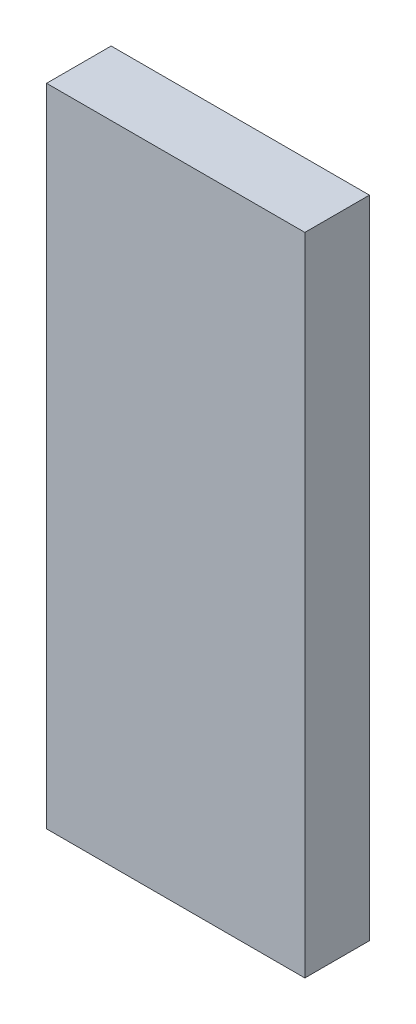
SolidWorks part; units mm, degrees
ref_plane "Front Plane" through (0, 0, 0) normal (0, 0, 1) x (1, 0, 0)
ref_plane "Top Plane" through (0, 0, 0) normal (0, 1, 0) x (1, 0, 0)
ref_plane "Right Plane" through (0, 0, 0) normal (1, 0, 0) x (0, 0, -1)
sketch "Sketch1" plane through (0, 0, 0) normal (0, 0, 1) x (1, 0, 0)
  line L1 (-100, 250) -> (100, 250)
  line L2 (-100, 250) -> (-100, -250)
  line L3 (-100, -250) -> (100, -250)
  line L4 (100, 250) -> (100, -250)
  line L5 (-100, 250) -> (100, -250) construction
  line L6 (-100, -250) -> (100, 250) construction
  point P0 (0, 0)
  dimension "D1" = 500
  dimension "D2" = 200
extrude "Boss-Extrude1" add sketch "Sketch1" along normal blind 50
sketch "Sketch2" plane through (0, 0, 0) normal (0, 0, -1) x (-1, 0, 0)
  line L0 (-77.8321, -160.6844) -> (-36, -160.6844)
  line L1 (-36, -250) -> (-36, 250) construction
  line L2 (90, -250) -> (90, 250) construction
  line L3 (27, -250) -> (27, 250) construction
  line L4 (-100, 250) -> (-100, -250)
  line L5 (-100, -250) -> (100, -250)
  line L6 (100, -250) -> (100, 250)
  line L7 (100, 250) -> (-100, 250)
  line L8 (-100, 250) -> (-100, -250)
  line L9 (-100, -250) -> (100, -250)
  line L10 (100, -250) -> (100, 250)
  line L11 (100, 250) -> (-100, 250)
  line L12 (-36, -160.6844) -> (-36, -170.0351)
  line L13 (-36, -170.0351) -> (-55.0167, -175.9408)
  line L14 (-55.0167, -175.9408) -> (-36, -175.9408)
  line L15 (-36, -175.9408) -> (-36, -185.2915)
  line L16 (-36, -185.2915) -> (-77.8321, -185.2915)
  line L17 (-77.8321, -185.2915) -> (-77.8321, -175.9408)
  line L18 (-77.8321, -175.9408) -> (-58.9923, -170.0351)
  line L19 (-58.9923, -170.0351) -> (-77.8321, -170.0351)
  line L20 (-77.8321, -170.0351) -> (-77.8321, -160.6844)
  line L21 (-62.5757, -130.6637) -> (-62.5757, -141.4908)
  line L22 (-62.5757, -141.4908) -> (-66.4359, -141.4908)
  line L23 (-67.0742, -145.428) -> (-46.5964, -145.428)
  line L24 (-47.0578, -140.9987) -> (-52.2407, -140.9987)
  line L25 (-52.2407, -140.9987) -> (-52.2407, -143.4594)
  line L26 (-52.2407, -143.4594) -> (-58.6385, -143.4594)
  line L27 (-58.6385, -143.4594) -> (-58.6385, -130.6637)
  line L28 (-58.6385, -130.6637) -> (-36, -130.6637)
  line L29 (-36, -130.6637) -> (-36, -137.3153)
  line L30 (-36, -137.3153) -> (-39.0144, -138.2919)
  line L31 (-50.3106, -156.2551) -> (-62.7987, -156.2551)
  line L32 (-64.3828, -130.6637) -> (-62.5757, -130.6637)
  line L33 (-77.8321, -101.6273) -> (-49.803, -101.6273)
  line L34 (-53.0173, -126.7266) -> (-77.8321, -126.7266)
  line L35 (-77.8321, -126.7266) -> (-77.8321, -115.8994)
  line L36 (-77.8321, -115.8994) -> (-46.2043, -115.8994)
  line L37 (-46.7502, -112.4545) -> (-77.8321, -112.4545)
  line L38 (-77.8321, -112.4545) -> (-77.8321, -101.6273)
  line L39 (-77.8321, -74.0674) -> (-51.1411, -81.9416)
  line L40 (-51.1411, -81.9416) -> (-36, -81.9416)
  line L41 (-36, -81.9416) -> (-36, -92.2766)
  line L42 (-36, -92.2766) -> (-51.1411, -92.2766)
  line L43 (-51.1411, -92.2766) -> (-77.8321, -100.1509)
  line L44 (-77.8321, -100.1509) -> (-77.8321, -90.4311)
  line L45 (-77.8321, -83.7872) -> (-77.8321, -74.0674)
  line L46 (-77.8321, -72.5909) -> (-77.8321, -53.8896)
  line L47 (-77.8321, -53.8896) -> (-69.4657, -53.8896)
  line L48 (-69.4657, -53.8896) -> (-69.4657, -61.7638)
  line L49 (-69.4657, -61.7638) -> (-61.5914, -61.7638)
  line L50 (-61.5914, -61.7638) -> (-61.5914, -54.3817)
  line L51 (-61.5914, -54.3817) -> (-53.7171, -54.3817)
  line L52 (-53.7171, -54.3817) -> (-53.7171, -61.7638)
  line L53 (-53.7171, -61.7638) -> (-44.3664, -61.7638)
  line L54 (-44.3664, -61.7638) -> (-44.3664, -53.3974)
  line L55 (-44.3664, -53.3974) -> (-36, -53.3974)
  line L56 (-36, -53.3974) -> (-36, -72.5909)
  line L57 (-36, -72.5909) -> (-77.8321, -72.5909)
  line L58 (-77.8321, -25.8375) -> (-36, -25.8375)
  line L59 (-36, -25.8375) -> (-36, -35.1882)
  line L60 (-36, -35.1882) -> (-55.0167, -41.0939)
  line L61 (-55.0167, -41.0939) -> (-36, -41.0939)
  line L62 (-36, -41.0939) -> (-36, -50.4446)
  line L63 (-36, -50.4446) -> (-77.8321, -50.4446)
  line L64 (-77.8321, -50.4446) -> (-77.8321, -41.0939)
  line L65 (-77.8321, -41.0939) -> (-58.9923, -35.1882)
  line L66 (-58.9923, -35.1882) -> (-77.8321, -35.1882)
  line L67 (-77.8321, -35.1882) -> (-77.8321, -25.8375)
  line L68 (-77.8321, -12.0575) -> (-77.8321, -0.9612)
  line L69 (-49.8799, 13.5339) -> (-45.9505, 13.5339)
  line L70 (-36, 0.6613) -> (-36, -12.0575)
  line L71 (-36, -12.0575) -> (-77.8321, -12.0575)
  line L72 (-70.9421, -1.2304) -> (-61.5914, -1.2304)
  line L73 (-55.1935, -1.2304) -> (-42.89, -1.2304)
  line L74 (-46.9886, 2.7068) -> (-51.0949, 2.7068)
  line L75 (-77.8321, 36.0494) -> (-36, 42.5703)
  line L76 (-36, 42.5703) -> (-36, 31.3741)
  line L77 (-36, 31.3741) -> (-43.3821, 30.7512)
  line L78 (-43.3821, 30.7512) -> (-43.3821, 26.3604)
  line L79 (-43.3821, 26.3604) -> (-36, 25.7144)
  line L80 (-36, 25.7144) -> (-36, 14.5182)
  line L81 (-36, 14.5182) -> (-77.8321, 20.0548)
  line L82 (-77.8321, 20.0548) -> (-77.8321, 36.0494)
  line L83 (-50.7643, 26.3757) -> (-50.7643, 30.2437)
  line L84 (-53.3172, 44.5389) -> (-60.5148, 44.5389)
  line L85 (-60.5148, 69.6381) -> (-53.3172, 69.6381)
  line L86 (-67.2895, 55.366) -> (-47.3654, 55.366)
  line L87 (-47.6807, 58.811) -> (-67.2895, 58.811)
  line L88 (-77.8321, 93.7531) -> (-44.3664, 93.7531)
  line L89 (-44.3664, 93.7531) -> (-44.3664, 100.643)
  line L90 (-44.3664, 100.643) -> (-36, 100.643)
  line L91 (-36, 100.643) -> (-36, 82.9259)
  line L92 (-36, 82.9259) -> (-77.8321, 82.9259)
  line L93 (-77.8321, 82.9259) -> (-77.8321, 93.7531)
  line L94 (-53.3172, 103.1038) -> (-60.5148, 103.1038)
  line L95 (-60.5148, 128.203) -> (-53.3172, 128.203)
  line L96 (-67.2895, 113.9309) -> (-47.3654, 113.9309)
  line L97 (-47.6807, 117.3759) -> (-67.2895, 117.3759)
  line L98 (-77.8321, 156.7472) -> (-36, 156.7472)
  line L99 (-36, 156.7472) -> (-36, 147.3965)
  line L100 (-36, 147.3965) -> (-55.0167, 141.4908)
  line L101 (-55.0167, 141.4908) -> (-36, 141.4908)
  line L102 (-36, 141.4908) -> (-36, 132.1401)
  line L103 (-36, 132.1401) -> (-77.8321, 132.1401)
  line L104 (-77.8321, 132.1401) -> (-77.8321, 141.4908)
  line L105 (-77.8321, 141.4908) -> (-58.9923, 147.3965)
  line L106 (-58.9923, 147.3965) -> (-77.8321, 147.3965)
  line L107 (-77.8321, 147.3965) -> (-77.8321, 156.7472)
  line L108 (-62.5757, 186.7679) -> (-62.5757, 175.9408)
  line L109 (-62.5757, 175.9408) -> (-66.4359, 175.9408)
  line L110 (-67.0742, 172.0036) -> (-46.5964, 172.0036)
  line L111 (-47.0578, 176.4329) -> (-52.2407, 176.4329)
  line L112 (-52.2407, 176.4329) -> (-52.2407, 173.9722)
  line L113 (-52.2407, 173.9722) -> (-58.6385, 173.9722)
  line L114 (-58.6385, 173.9722) -> (-58.6385, 186.7679)
  line L115 (-58.6385, 186.7679) -> (-36, 186.7679)
  line L116 (-36, 186.7679) -> (-36, 180.1163)
  line L117 (-36, 180.1163) -> (-39.0144, 179.1397)
  line L118 (-50.3106, 161.1765) -> (-62.7987, 161.1765)
  line L119 (-64.3828, 186.7679) -> (-62.5757, 186.7679)
  line L120 (-14.8321, -176.5703) -> (27, -176.5703)
  line L121 (27, -176.5703) -> (27, -187.6439)
  line L122 (27, -187.6439) -> (8.4249, -191.6493)
  line L123 (8.4249, -191.6493) -> (27, -191.6493)
  line L124 (27, -191.6493) -> (27, -201.8641)
  line L125 (27, -201.8641) -> (-14.8321, -201.8641)
  line L126 (-14.8321, -201.8641) -> (-14.8321, -191.3148)
  line L127 (-14.8321, -191.3148) -> (3.5683, -186.7851)
  line L128 (3.5683, -186.7851) -> (-14.8321, -186.7851)
  line L129 (-14.8321, -186.7851) -> (-14.8321, -176.5703)
  line L130 (1.2198, -146.8987) -> (1.2198, -159.0592)
  line L131 (1.2198, -159.0592) -> (-3.082, -159.0592)
  line L132 (-3.7964, -160.5184) -> (16.1164, -160.5184)
  line L133 (15.5843, -158.5727) -> (10.9482, -158.5727)
  line L134 (10.9482, -158.5727) -> (10.9482, -160.5184)
  line L135 (10.9482, -160.5184) -> (4.1383, -160.5184)
  line L136 (4.1383, -160.5184) -> (4.1383, -146.8987)
  line L137 (4.1383, -146.8987) -> (27, -146.8987)
  line L138 (27, -146.8987) -> (27, -154.803)
  line L139 (27, -154.803) -> (24.0815, -155.3806)
  line L140 (12.5442, -172.6789) -> (0.3381, -172.6789)
  line L141 (-1.0527, -146.8987) -> (1.2198, -146.8987)
  line L142 (-14.8321, -117.2271) -> (13.0382, -117.2271)
  line L143 (9.8993, -143.0073) -> (-14.8321, -143.0073)
  line L144 (-14.8321, -143.0073) -> (-14.8321, -130.8468)
  line L145 (-14.8321, -130.8468) -> (16.4888, -130.8468)
  line L146 (15.9492, -129.3876) -> (-14.8321, -129.3876)
  line L147 (-14.8321, -129.3876) -> (-14.8321, -117.2271)
  line L148 (-14.8321, -89.5012) -> (11.7234, -97.2839)
  line L149 (11.7234, -97.2839) -> (27, -97.2839)
  line L150 (27, -97.2839) -> (27, -108.4715)
  line L151 (27, -108.4715) -> (11.807, -108.4715)
  line L152 (11.807, -108.4715) -> (-14.8321, -115.7678)
  line L153 (-14.8321, -115.7678) -> (-14.8321, -104.7702)
  line L154 (-14.8321, -100.4988) -> (-14.8321, -89.5012)
  line L155 (-14.8321, -88.5283) -> (-14.8321, -69.0716)
  line L156 (-14.8321, -69.0716) -> (-5.5901, -69.0716)
  line L157 (-5.5901, -69.0716) -> (-5.5901, -76.3679)
  line L158 (-5.5901, -76.3679) -> (1.2198, -76.3679)
  line L159 (1.2198, -76.3679) -> (1.2198, -69.558)
  line L160 (1.2198, -69.558) -> (9.9753, -69.558)
  line L161 (9.9753, -69.558) -> (9.9753, -76.3679)
  line L162 (9.9753, -76.3679) -> (17.758, -76.3679)
  line L163 (17.758, -76.3679) -> (17.758, -68.5851)
  line L164 (17.758, -68.5851) -> (27, -68.5851)
  line L165 (27, -68.5851) -> (27, -88.5283)
  line L166 (27, -88.5283) -> (-14.8321, -88.5283)
  line L167 (-14.8321, -40.8592) -> (27, -40.8592)
  line L168 (27, -40.8592) -> (27, -51.9329)
  line L169 (27, -51.9329) -> (8.4249, -55.9382)
  line L170 (8.4249, -55.9382) -> (27, -55.9382)
  line L171 (27, -55.9382) -> (27, -66.153)
  line L172 (27, -66.153) -> (-14.8321, -66.153)
  line L173 (-14.8321, -66.153) -> (-14.8321, -55.6038)
  line L174 (-14.8321, -55.6038) -> (3.5683, -51.074)
  line L175 (3.5683, -51.074) -> (-14.8321, -51.074)
  line L176 (-14.8321, -51.074) -> (-14.8321, -40.8592)
  line L177 (-14.8321, -0.9728) -> (27, -0.9728)
  line L178 (27, -0.9728) -> (27, -13.1333)
  line L179 (27, -13.1333) -> (9.9753, -13.1333)
  line L180 (9.9753, -13.1333) -> (9.9753, -15.079)
  line L181 (9.9753, -15.079) -> (27, -15.079)
  line L182 (27, -15.079) -> (27, -27.2395)
  line L183 (27, -27.2395) -> (-14.8321, -27.2395)
  line L184 (-14.8321, -27.2395) -> (-14.8321, -15.079)
  line L185 (-14.8321, -15.079) -> (-0.2395, -15.079)
  line L186 (-0.2395, -15.079) -> (-0.2395, -13.1333)
  line L187 (-0.2395, -13.1333) -> (-14.8321, -13.1333)
  line L188 (-14.8321, -13.1333) -> (-14.8321, -0.9728)
  line L189 (-14.8321, 28.2123) -> (13.0382, 28.2123)
  line L190 (9.8993, 2.4321) -> (-14.8321, 2.4321)
  line L191 (-14.8321, 2.4321) -> (-14.8321, 14.5926)
  line L192 (-14.8321, 14.5926) -> (16.4888, 14.5926)
  line L193 (15.9492, 16.0518) -> (-14.8321, 16.0518)
  line L194 (-14.8321, 16.0518) -> (-14.8321, 28.2123)
  line L195 (-14.8321, 55.9382) -> (11.7234, 48.1555)
  line L196 (11.7234, 48.1555) -> (27, 48.1555)
  line L197 (27, 48.1555) -> (27, 36.9679)
  line L198 (27, 36.9679) -> (11.807, 36.9679)
  line L199 (11.807, 36.9679) -> (-14.8321, 29.6716)
  line L200 (-14.8321, 29.6716) -> (-14.8321, 40.6692)
  line L201 (-14.8321, 44.9406) -> (-14.8321, 55.9382)
  line L202 (-14.8321, 89.5012) -> (-5.5901, 89.5012)
  line L203 (-5.5901, 89.5012) -> (-5.5901, 83.6641)
  line L204 (-5.5901, 83.6641) -> (27, 83.6641)
  line L205 (27, 83.6641) -> (27, 71.5037)
  line L206 (27, 71.5037) -> (-5.5901, 71.5037)
  line L207 (-5.5901, 71.5037) -> (-5.5901, 65.1802)
  line L208 (-5.5901, 65.1802) -> (-14.8321, 65.1802)
  line L209 (-14.8321, 65.1802) -> (-14.8321, 89.5012)
  line L210 (-14.8321, 117.7135) -> (27, 117.7135)
  line L211 (27, 117.7135) -> (27, 105.553)
  line L212 (27, 105.553) -> (9.9753, 105.553)
  line L213 (9.9753, 105.553) -> (9.9753, 103.6073)
  line L214 (9.9753, 103.6073) -> (27, 103.6073)
  line L215 (27, 103.6073) -> (27, 91.4469)
  line L216 (27, 91.4469) -> (-14.8321, 91.4469)
  line L217 (-14.8321, 91.4469) -> (-14.8321, 103.6073)
  line L218 (-14.8321, 103.6073) -> (-0.2395, 103.6073)
  line L219 (-0.2395, 103.6073) -> (-0.2395, 105.553)
  line L220 (-0.2395, 105.553) -> (-14.8321, 105.553)
  line L221 (-14.8321, 105.553) -> (-14.8321, 117.7135)
  line L222 (-14.8321, 140.864) -> (27, 147.1419)
  line L223 (27, 147.1419) -> (27, 134.8978)
  line L224 (27, 134.8978) -> (19.7037, 134.2746)
  line L225 (19.7037, 134.2746) -> (19.7037, 131.318)
  line L226 (19.7037, 131.318) -> (27, 130.672)
  line L227 (27, 130.672) -> (27, 118.4431)
  line L228 (27, 118.4431) -> (-14.8321, 124.2194)
  line L229 (-14.8321, 124.2194) -> (-14.8321, 140.864)
  line L230 (11.4346, 131.3941) -> (11.4346, 133.7273)
  line L231 (-14.8321, 173.6517) -> (27, 173.6517)
  line L232 (27, 173.6517) -> (27, 162.5781)
  line L233 (27, 162.5781) -> (8.4249, 158.5727)
  line L234 (8.4249, 158.5727) -> (27, 158.5727)
  line L235 (27, 158.5727) -> (27, 148.3579)
  line L236 (27, 148.3579) -> (-14.8321, 148.3579)
  line L237 (-14.8321, 148.3579) -> (-14.8321, 158.9072)
  line L238 (-14.8321, 158.9072) -> (3.5683, 163.4369)
  line L239 (3.5683, 163.4369) -> (-14.8321, 163.4369)
  line L240 (-14.8321, 163.4369) -> (-14.8321, 173.6517)
  line L241 (1.2198, 203.3233) -> (1.2198, 191.1628)
  line L242 (1.2198, 191.1628) -> (-3.082, 191.1628)
  line L243 (-3.7964, 189.7036) -> (16.1164, 189.7036)
  line L244 (15.5843, 191.6493) -> (10.9482, 191.6493)
  line L245 (10.9482, 191.6493) -> (10.9482, 189.7036)
  line L246 (10.9482, 189.7036) -> (4.1383, 189.7036)
  line L247 (4.1383, 189.7036) -> (4.1383, 203.3233)
  line L248 (4.1383, 203.3233) -> (27, 203.3233)
  line L249 (27, 203.3233) -> (27, 195.419)
  line L250 (27, 195.419) -> (24.0815, 194.8414)
  line L251 (12.5442, 177.5431) -> (0.3381, 177.5431)
  line L252 (-1.0527, 203.3233) -> (1.2198, 203.3233)
  line L253 (48.1679, -119.3444) -> (90, -119.3444)
  line L254 (90, -119.3444) -> (90, -128.6951)
  line L255 (90, -128.6951) -> (61.7557, -128.9412)
  line L256 (61.7557, -128.9412) -> (90, -132.6323)
  line L257 (90, -132.6323) -> (90, -140.0144)
  line L258 (90, -140.0144) -> (62.2478, -143.7055)
  line L259 (62.2478, -143.7055) -> (90, -143.9515)
  line L260 (90, -143.9515) -> (90, -153.3022)
  line L261 (90, -153.3022) -> (48.1679, -153.3022)
  line L262 (48.1679, -153.3022) -> (48.1679, -139.6453)
  line L263 (56.9957, -138.1227) -> (67.6998, -136.3233)
  line L264 (67.6998, -136.3233) -> (48.1679, -133.4935)
  line L265 (48.1679, -133.4935) -> (48.1679, -119.3444)
  line L266 (48.1679, -96.8289) -> (90, -90.3081)
  line L267 (90, -90.3081) -> (90, -101.5043)
  line L268 (90, -101.5043) -> (82.6179, -102.1272)
  line L269 (82.6179, -102.1272) -> (82.6179, -106.518)
  line L270 (82.6179, -106.518) -> (90, -107.1639)
  line L271 (90, -107.1639) -> (90, -118.3602)
  line L272 (90, -118.3602) -> (48.1679, -112.8236)
  line L273 (48.1679, -112.8236) -> (48.1679, -96.8289)
  line L274 (75.2357, -106.5026) -> (75.2357, -102.6347)
  line L275 (48.1679, -77.5124) -> (90, -77.5124)
  line L276 (90, -77.5124) -> (90, -88.3395)
  line L277 (90, -88.3395) -> (48.1679, -88.3395)
  line L278 (48.1679, -88.3395) -> (48.1679, -77.5124)
  line L279 (90, -38.6331) -> (94.9214, -38.6331)
  line L280 (94.9214, -38.6331) -> (94.9214, -46.7381)
  line L281 (74.8974, -63.7324) -> (61.9248, -63.7324)
  line L282 (61.6557, -38.6331) -> (75.2511, -38.6331)
  line L283 (90, -42.4857) -> (90, -38.6331)
  line L284 (58.6336, -52.9053) -> (78.2347, -52.9053)
  line L285 (77.9271, -49.4603) -> (58.6336, -49.4603)
  line L286 (48.1679, -9.5968) -> (76.197, -9.5968)
  line L287 (72.9827, -34.696) -> (48.1679, -34.696)
  line L288 (48.1679, -34.696) -> (48.1679, -23.8689)
  line L289 (48.1679, -23.8689) -> (79.7957, -23.8689)
  line L290 (79.2498, -20.4239) -> (48.1679, -20.4239)
  line L291 (48.1679, -20.4239) -> (48.1679, -9.5968)
  line L292 (72.6828, -5.6596) -> (65.4852, -5.6596)
  line L293 (65.4852, 19.4396) -> (72.6828, 19.4396)
  line L294 (58.7105, 5.1675) -> (78.6346, 5.1675)
  line L295 (78.3193, 8.6125) -> (58.7105, 8.6125)
  line L296 (65.885, 48.9681) -> (65.885, 38.141)
  line L297 (65.885, 38.141) -> (58.7336, 38.141)
  line L298 (59.2642, 34.2039) -> (79.0883, 34.2039)
  line L299 (78.4039, 38.141) -> (72.775, 38.141)
  line L300 (72.775, 38.141) -> (72.775, 48.9681)
  line L301 (72.775, 48.9681) -> (74.4591, 48.9681)
  line L302 (75.1742, 23.3767) -> (62.8937, 23.3767)
  line L303 (61.994, 48.9681) -> (65.885, 48.9681)
  line L304 (48.1679, 87.8474) -> (90, 87.8474)
  line L305 (90, 87.8474) -> (90, 77.0202)
  line L306 (90, 77.0202) -> (72.2829, 77.0202)
  line L307 (72.2829, 77.0202) -> (72.2829, 73.0831)
  line L308 (72.2829, 73.0831) -> (90, 73.0831)
  line L309 (90, 73.0831) -> (90, 62.256)
  line L310 (90, 62.256) -> (48.1679, 62.256)
  line L311 (48.1679, 62.256) -> (48.1679, 73.0831)
  line L312 (48.1679, 73.0831) -> (62.9322, 73.0831)
  line L313 (62.9322, 73.0831) -> (62.9322, 77.0202)
  line L314 (62.9322, 77.0202) -> (48.1679, 77.0202)
  line L315 (48.1679, 77.0202) -> (48.1679, 87.8474)
  line L316 (48.1679, 102.6116) -> (90, 102.6116)
  line L317 (90, 102.6116) -> (90, 91.7845)
  line L318 (90, 91.7845) -> (48.1679, 91.7845)
  line L319 (48.1679, 91.7845) -> (48.1679, 102.6116)
  line L320 (48.1679, 107.0409) -> (48.1679, 125.7423)
  line L321 (48.1679, 125.7423) -> (56.5343, 125.7423)
  line L322 (56.5343, 125.7423) -> (56.5343, 117.868)
  line L323 (56.5343, 117.868) -> (64.4086, 117.868)
  line L324 (64.4086, 117.868) -> (64.4086, 125.2501)
  line L325 (64.4086, 125.2501) -> (72.2829, 125.2501)
  line L326 (72.2829, 125.2501) -> (72.2829, 117.868)
  line L327 (72.2829, 117.868) -> (81.6336, 117.868)
  line L328 (81.6336, 117.868) -> (81.6336, 126.2344)
  line L329 (81.6336, 126.2344) -> (90, 126.2344)
  line L330 (90, 126.2344) -> (90, 107.0409)
  line L331 (90, 107.0409) -> (48.1679, 107.0409)
  line L332 (48.1679, 154.2865) -> (76.197, 154.2865)
  line L333 (72.9827, 129.1873) -> (48.1679, 129.1873)
  line L334 (48.1679, 129.1873) -> (48.1679, 140.0144)
  line L335 (48.1679, 140.0144) -> (79.7957, 140.0144)
  line L336 (79.2498, 143.4594) -> (48.1679, 143.4594)
  line L337 (48.1679, 143.4594) -> (48.1679, 154.2865)
  spline S0 degree 3 poles (-66.4359, -141.4908) (-66.9871, -141.4927) (-67.7716, -141.5033) (-68.7611, -141.5327) (-69.377, -141.5679) (-69.9068, -141.6269) (-70.3522, -141.673) (-70.7127, -141.7418) (-71.0687, -141.8451) (-71.4299, -142.0414) (-71.8522, -142.5863) (-71.9337, -143.1268) (-71.9264, -143.4902) knots 0 0 0 0 0.249728 0.355472 0.448565 0.529113 0.596963 0.6514 0.695118 0.764841 0.833402 1 1 1 1
  spline S1 degree 3 poles (-71.9264, -143.4902) (-71.9417, -143.8157) (-71.8475, -144.2898) (-71.4991, -144.7997) (-71.1907, -145.0167) (-70.8747, -145.1317) (-70.5585, -145.2155) (-70.1646, -145.282) (-69.6944, -145.332) (-69.1485, -145.3798) (-68.2665, -145.4207) (-67.5663, -145.423) (-67.0742, -145.428) knots 0 0 0 0 0.164556 0.236223 0.307889 0.351033 0.406129 0.473344 0.553035 0.645513 0.75077 1 1 1 1
  spline S2 degree 3 poles (-46.5964, -145.428) (-46.1584, -145.4182) (-45.5315, -145.4287) (-44.7401, -145.3696) (-44.2377, -145.3236) (-43.7954, -145.2747) (-43.4129, -145.2042) (-43.0919, -145.1252) (-42.7547, -144.9936) (-42.4067, -144.7762) (-41.9868, -144.2336) (-41.8961, -143.7008) (-41.9057, -143.3441) knots 0 0 0 0 0.225316 0.321712 0.407708 0.484672 0.550305 0.607502 0.654229 0.736078 0.81488 1 1 1 1
  spline S3 degree 3 poles (-41.9057, -143.3441) (-41.9166, -142.9585) (-41.9978, -142.3576) (-42.4853, -141.7627) (-42.8828, -141.5125) (-43.2687, -141.3631) (-43.6278, -141.268) (-44.0488, -141.1824) (-44.5293, -141.1165) (-45.073, -141.0624) (-45.9215, -141.0108) (-46.5912, -140.9987) (-47.0578, -140.9987) knots 0 0 0 0 0.184659 0.266523 0.35236 0.401363 0.459856 0.525958 0.602293 0.686676 0.781625 1 1 1 1
  spline S4 degree 3 poles (-39.0144, -138.2919) (-38.3973, -138.6583) (-37.5285, -139.2846) (-36.592, -140.3284) (-36.0158, -141.172) (-35.5693, -142.0954) (-35.1191, -143.4594) (-35.0164, -144.5595) (-35.0157, -145.3049) knots 0 0 0 0 0.254087 0.374684 0.494032 0.613957 0.735995 1 1 1 1
  spline S5 degree 3 poles (-35.0157, -145.3049) (-35.0196, -146.2225) (-35.1727, -147.6035) (-35.7443, -149.3553) (-36.3264, -150.599) (-37.0292, -151.7443) (-37.8185, -152.7659) (-38.6948, -153.6374) (-39.6452, -154.3564) (-40.6491, -154.9246) (-41.6713, -155.3996) (-42.7269, -155.7336) (-43.6357, -155.9228) (-44.4036, -156.0232) (-45.0478, -156.0816) (-45.7578, -156.1353) (-46.537, -156.1835) (-47.3858, -156.2104) (-48.6519, -156.2432) (-49.6338, -156.2524) (-50.3106, -156.2551) knots 0 0 0 0 0.127853 0.191619 0.255803 0.318602 0.378355 0.435135 0.490166 0.543728 0.595475 0.646827 0.697502 0.724505 0.754618 0.787546 0.823655 0.863294 0.905777 1 1 1 1
  spline S6 degree 3 poles (-62.7987, -156.2551) (-63.7343, -156.2561) (-65.086, -156.2445) (-66.8183, -156.167) (-67.9647, -156.1012) (-69.0087, -156.0113) (-69.9494, -155.8941) (-70.7869, -155.7683) (-71.5383, -155.6135) (-72.2328, -155.4156) (-72.8924, -155.1303) (-73.5433, -154.7789) (-74.1679, -154.3308) (-74.7997, -153.8366) (-75.3965, -153.2416) (-75.9893, -152.5811) (-76.5642, -151.8487) (-77.0933, -151.046) (-77.5546, -150.1805) (-77.9521, -149.2616) (-78.2603, -148.28) (-78.5187, -147.2491) (-78.758, -145.7629) (-78.8066, -144.6113) (-78.8164, -143.8285) knots 0 0 0 0 0.118708 0.171437 0.219978 0.264375 0.304346 0.34022 0.371789 0.401628 0.431646 0.462789 0.495264 0.529036 0.56445 0.601987 0.641602 0.682459 0.723777 0.765878 0.809275 0.854152 0.900609 1 1 1 1
  spline S7 degree 3 poles (-78.8164, -143.8285) (-78.8154, -143.0532) (-78.7624, -141.9142) (-78.5527, -140.4392) (-78.3384, -139.4061) (-78.0621, -138.4251) (-77.7321, -137.4921) (-77.332, -136.6153) (-76.87, -135.7966) (-76.3717, -135.0379) (-75.847, -134.34) (-75.2971, -133.7125) (-74.7248, -133.1532) (-74.131, -132.6659) (-73.5135, -132.2484) (-72.8728, -131.8989) (-72.1978, -131.6211) (-71.4761, -131.3843) (-70.6841, -131.201) (-69.8207, -131.029) (-68.8816, -130.8903) (-67.8647, -130.7967) (-66.3585, -130.6872) (-65.1878, -130.6652) (-64.3828, -130.6637) knots 0 0 0 0 0.102699 0.150706 0.197176 0.242313 0.285584 0.328118 0.369761 0.409964 0.448255 0.485298 0.520346 0.554119 0.586883 0.618933 0.650581 0.68343 0.719409 0.758155 0.800017 0.845043 0.893365 1 1 1 1
  spline S8 degree 3 poles (-49.803, -101.6273) (-49.0674, -101.6302) (-48.0086, -101.6388) (-46.6578, -101.6716) (-45.7783, -101.6989) (-44.9863, -101.7466) (-44.2812, -101.7996) (-43.665, -101.8573) (-42.958, -101.96) (-42.117, -102.1544) (-41.1266, -102.5495) (-40.1247, -103.0937) (-39.1277, -103.7785) (-38.1777, -104.5991) (-37.3353, -105.5577) (-36.6193, -106.6418) (-36.0378, -107.8492) (-35.5768, -109.1698) (-35.1206, -111.1416) (-35.0267, -112.7029) (-35.0157, -113.7694) knots 0 0 0 0 0.098874 0.142291 0.181587 0.217129 0.248914 0.27661 0.300287 0.344906 0.392245 0.443108 0.497859 0.554506 0.61138 0.668802 0.72858 0.791008 0.856437 1 1 1 1
  spline S9 degree 3 poles (-35.0157, -113.7694) (-35.018, -114.9608) (-35.1449, -116.7128) (-35.6798, -118.9324) (-36.2243, -120.4287) (-36.889, -121.7792) (-37.6486, -122.9669) (-38.5058, -123.9775) (-39.4671, -124.7856) (-40.4845, -125.4225) (-41.5248, -125.934) (-42.6039, -126.278) (-43.5454, -126.4589) (-44.3863, -126.5331) (-45.1682, -126.5856) (-46.1039, -126.6335) (-47.1911, -126.6575) (-48.4316, -126.6915) (-50.3899, -126.7249) (-51.9357, -126.716) (-53.0173, -126.7266) knots 0 0 0 0 0.136523 0.199943 0.260844 0.31846 0.37194 0.421883 0.469567 0.515078 0.559049 0.601925 0.644344 0.668522 0.698526 0.734079 0.775768 0.823031 0.876156 1 1 1 1
  spline S10 degree 3 poles (-46.2043, -115.8994) (-45.7862, -115.8992) (-45.1892, -115.8842) (-44.4348, -115.8605) (-43.9617, -115.8135) (-43.5487, -115.7881) (-43.2022, -115.7179) (-42.9139, -115.6642) (-42.6217, -115.5648) (-42.3258, -115.3914) (-41.9784, -114.9573) (-41.8967, -114.5312) (-41.9057, -114.2462) knots 0 0 0 0 0.241402 0.345146 0.435772 0.516072 0.583748 0.6398 0.685221 0.761661 0.834276 1 1 1 1
  spline S11 degree 3 poles (-41.9057, -114.2462) (-41.9194, -113.9364) (-41.9615, -113.4367) (-42.3738, -112.9788) (-42.6945, -112.7936) (-43.0203, -112.6988) (-43.3413, -112.6302) (-43.7351, -112.5808) (-44.1992, -112.5347) (-44.735, -112.4955) (-45.594, -112.4678) (-46.2734, -112.4558) (-46.7502, -112.4545) knots 0 0 0 0 0.166051 0.236159 0.309458 0.35368 0.410337 0.478239 0.557776 0.650343 0.754622 1 1 1 1
  spline S12 degree 3 poles (-77.8321, -90.4311) (-76.8129, -90.2461) (-75.3145, -89.9904) (-73.364, -89.6437) (-72.0003, -89.3979) (-70.7067, -89.1576) (-69.4771, -88.9392) (-68.318, -88.71) (-67.2218, -88.5087) (-66.1981, -88.3033) (-65.2398, -88.1245) (-64.3525, -87.9345) (-63.525, -87.7706) (-62.7703, -87.5993) (-61.8958, -87.4011) (-61.2726, -87.2699) (-60.8839, -87.163) knots 0 0 0 0 0.180008 0.264154 0.344276 0.420812 0.492806 0.561297 0.626121 0.686487 0.742747 0.795513 0.844172 0.889347 0.92998 1 1 1 1
  spline S13 degree 3 poles (-60.8839, -87.163) (-62.0559, -86.8718) (-63.8806, -86.4592) (-66.3926, -85.9214) (-68.454, -85.5061) (-70.6308, -85.086) (-73.7684, -84.4958) (-76.1814, -84.0652) (-77.8321, -83.7872) knots 0 0 0 0 0.209587 0.32468 0.445872 0.57457 0.709469 1 1 1 1
  spline S14 degree 3 poles (-77.8321, -0.9612) (-77.8226, -0.1384) (-77.8155, 1.0572) (-77.7331, 2.5979) (-77.6378, 3.6332) (-77.5329, 4.5902) (-77.4056, 5.4687) (-77.244, 6.2664) (-77.0601, 6.9947) (-76.8359, 7.6676) (-76.5587, 8.2973) (-76.2329, 8.8931) (-75.8633, 9.4588) (-75.4377, 9.9909) (-74.9616, 10.49) (-74.4332, 10.9543) (-73.8532, 11.3893) (-73.2017, 11.7886) (-72.4569, 12.1248) (-71.6186, 12.4067) (-70.694, 12.6445) (-69.6748, 12.8169) (-68.1406, 12.9951) (-66.937, 13.0509) (-66.1053, 13.0418) knots 0 0 0 0 0.114375 0.166108 0.21439 0.258844 0.299904 0.337701 0.371916 0.404248 0.43615 0.467396 0.498519 0.529953 0.561953 0.594259 0.627603 0.66261 0.70023 0.740899 0.785396 0.832777 0.884431 1 1 1 1
  spline S15 degree 3 poles (-66.1053, 13.0418) (-65.5481, 13.0506) (-64.7451, 13.0093) (-63.7264, 12.8811) (-63.0603, 12.7659) (-62.4664, 12.591) (-61.9337, 12.3994) (-61.4725, 12.1563) (-61.0678, 11.876) (-60.7151, 11.5302) (-60.3794, 11.1309) (-60.0873, 10.6471) (-59.7989, 10.1045) (-59.5283, 9.4896) (-59.209, 8.5258) (-58.9947, 7.7645) (-58.8846, 7.2283) knots 0 0 0 0 0.159635 0.229972 0.294227 0.35305 0.407212 0.456169 0.502024 0.547743 0.597307 0.65111 0.709269 0.77341 0.843331 1 1 1 1
  spline S16 degree 3 poles (-58.8846, 7.2283) (-58.7532, 7.8015) (-58.5177, 8.6263) (-58.0934, 9.6447) (-57.7583, 10.3125) (-57.3773, 10.8991) (-56.9721, 11.4205) (-56.5232, 11.864) (-56.0266, 12.2328) (-55.4788, 12.5405) (-54.8757, 12.8133) (-54.2036, 13.031) (-53.4689, 13.2158) (-52.6677, 13.3623) (-51.465, 13.4944) (-50.5267, 13.5319) (-49.8799, 13.5339) knots 0 0 0 0 0.144043 0.209309 0.269932 0.32668 0.380292 0.431325 0.480651 0.531247 0.584899 0.64245 0.703941 0.770287 0.841669 1 1 1 1
  spline S17 degree 3 poles (-45.9505, 13.5339) (-45.2812, 13.5334) (-44.3103, 13.5091) (-43.0624, 13.4032) (-42.2304, 13.2994) (-41.4681, 13.1598) (-40.7766, 12.9932) (-40.151, 12.795) (-39.4235, 12.4934) (-38.6215, 12.0286) (-37.8175, 11.3056) (-37.1849, 10.4323) (-36.7923, 9.5818) (-36.5664, 8.7828) (-36.4139, 8.0348) (-36.2889, 7.1486) (-36.1818, 6.12) (-36.1008, 4.9556) (-36.0118, 3.1206) (-36.0118, 1.6737) (-36, 0.6613) knots 0 0 0 0 0.102269 0.148253 0.191288 0.230306 0.266588 0.299901 0.330446 0.386794 0.440584 0.494395 0.550463 0.582684 0.621084 0.666995 0.719365 0.779044 0.845298 1 1 1 1
  spline S18 degree 2 poles (-61.5914, -1.2304) (-61.6074, -0.6306) (-61.6145, -0.0308) knots 0 0 0 1 1 1
  spline S19 degree 3 poles (-61.6145, -0.0308) (-61.6077, 0.455) (-61.6663, 1.1378) (-62.0201, 1.8973) (-62.3386, 2.2056) (-62.6737, 2.3522) (-63.0111, 2.4533) (-63.4435, 2.5202) (-63.9659, 2.5923) (-64.5795, 2.6425) (-65.5815, 2.6969) (-66.3795, 2.7059) (-66.9434, 2.7068) knots 0 0 0 0 0.207117 0.283923 0.350831 0.389245 0.438074 0.499907 0.574465 0.661754 0.760817 1 1 1 1
  spline S20 degree 3 poles (-66.9434, 2.7068) (-67.5041, 2.7131) (-68.276, 2.6736) (-69.204, 2.5125) (-69.6935, 2.331) (-70.0679, 2.1097) (-70.3597, 1.8598) (-70.5838, 1.5805) (-70.7303, 1.2437) (-70.8189, 0.8213) (-70.9164, -0.0094) (-70.9333, -0.7125) (-70.9421, -1.2304) knots 0 0 0 0 0.246774 0.340005 0.413619 0.475395 0.530632 0.582131 0.631661 0.690822 0.771636 1 1 1 1
  spline S21 degree 3 poles (-42.89, -1.2304) (-42.9077, -0.8458) (-42.9306, -0.2939) (-43.0298, 0.3966) (-43.1105, 0.8321) (-43.2191, 1.2095) (-43.3391, 1.5327) (-43.4747, 1.8011) (-43.6442, 2.0143) (-43.8591, 2.1823) (-44.1217, 2.3301) (-44.4522, 2.4386) (-44.839, 2.5413) (-45.2899, 2.6138) (-46.0127, 2.6863) (-46.5855, 2.7163) (-46.9886, 2.7068) knots 0 0 0 0 0.168584 0.241049 0.305039 0.362178 0.412572 0.455707 0.493181 0.530655 0.574326 0.624331 0.682257 0.749354 0.823771 1 1 1 1
  spline S22 degree 3 poles (-51.0949, 2.7068) (-51.5176, 2.7062) (-52.1228, 2.7003) (-52.8768, 2.6172) (-53.3445, 2.5661) (-53.7364, 2.4699) (-54.0648, 2.3682) (-54.3219, 2.2379) (-54.5242, 2.0857) (-54.6712, 1.8806) (-54.7899, 1.6241) (-54.8973, 1.3042) (-54.9861, 0.9202) (-55.0619, 0.4734) (-55.1476, -0.249) (-55.1788, -0.8249) (-55.1935, -1.2304) knots 0 0 0 0 0.182344 0.260037 0.326886 0.384748 0.433642 0.474638 0.508444 0.541576 0.582078 0.629925 0.686713 0.751712 0.825136 1 1 1 1
  spline S23 degree 3 poles (-50.7643, 30.2437) (-52.0609, 30.1192) (-54.0611, 29.9412) (-56.8005, 29.6776) (-59.0203, 29.4708) (-61.3533, 29.2573) (-64.6823, 28.9398) (-67.2356, 28.705) (-68.9735, 28.5442) knots 0 0 0 0 0.213674 0.3294 0.451445 0.57939 0.713693 1 1 1 1
  spline S24 degree 3 poles (-68.9735, 28.5442) (-67.0499, 28.3235) (-64.2678, 27.9775) (-60.6922, 27.5508) (-58.3124, 27.2779) (-56.1392, 27.0152) (-53.6461, 26.7101) (-51.8764, 26.5086) (-50.7643, 26.3757) knots 0 0 0 0 0.316757 0.458648 0.589098 0.708623 0.816757 1 1 1 1
  spline S25 degree 3 poles (-53.3172, 69.6381) (-52.3381, 69.6287) (-50.9282, 69.6343) (-49.1261, 69.605) (-47.9498, 69.5612) (-46.8856, 69.529) (-45.9372, 69.4738) (-45.1039, 69.4128) (-44.1538, 69.3264) (-43.0593, 69.1469) (-41.816, 68.7561) (-40.6334, 68.2058) (-39.5173, 67.5036) (-38.4836, 66.6635) (-37.5773, 65.6649) (-36.7941, 64.5335) (-36.1522, 63.2633) (-35.6345, 61.8798) (-35.1453, 59.8208) (-35.0067, 58.1993) (-35.0157, 57.0885) knots 0 0 0 0 0.113101 0.162848 0.208171 0.249056 0.285827 0.31789 0.345554 0.396029 0.44566 0.495598 0.546282 0.597611 0.648955 0.701516 0.75607 0.812935 0.871747 1 1 1 1
  spline S26 degree 3 poles (-35.0157, 57.0885) (-35.0166, 56.0226) (-35.1389, 54.4526) (-35.609, 52.4498) (-36.0939, 51.0736) (-36.6986, 49.794) (-37.4769, 48.6558) (-38.367, 47.6248) (-39.4108, 46.7577) (-40.5333, 46.0276) (-41.721, 45.4612) (-42.9558, 45.0555) (-44.0397, 44.856) (-44.9835, 44.7721) (-45.8141, 44.7101) (-46.7679, 44.6582) (-47.8418, 44.6103) (-49.0391, 44.583) (-50.8769, 44.5505) (-52.3176, 44.5416) (-53.3172, 44.5389) knots 0 0 0 0 0.123187 0.181008 0.237203 0.291505 0.343988 0.396026 0.44835 0.500181 0.550382 0.599921 0.649928 0.677302 0.709372 0.746151 0.787647 0.833563 0.884505 1 1 1 1
  spline S27 degree 3 poles (-60.5148, 44.5389) (-61.4914, 44.5483) (-62.9013, 44.5426) (-64.7034, 44.5721) (-65.8823, 44.6148) (-66.9437, 44.6508) (-67.8926, 44.6936) (-68.7255, 44.7569) (-69.679, 44.8413) (-70.7718, 45.0329) (-72.0165, 45.4197) (-73.1996, 45.9739) (-74.3206, 46.6686) (-75.3516, 47.5163) (-76.2501, 48.5183) (-77.0399, 49.6443) (-77.682, 50.9122) (-78.1862, 52.3023) (-78.6962, 54.3557) (-78.8051, 55.9828) (-78.8164, 57.0885) knots 0 0 0 0 0.112808 0.162853 0.208178 0.249064 0.285525 0.317884 0.345549 0.396077 0.445709 0.495649 0.546586 0.597688 0.649252 0.701572 0.756128 0.812892 0.872063 1 1 1 1
  spline S28 degree 3 poles (-78.8164, 57.0885) (-78.818, 58.1549) (-78.6889, 59.7203) (-78.231, 61.7225) (-77.7478, 63.0981) (-77.1292, 64.3739) (-76.3609, 65.5204) (-75.4617, 66.5441) (-74.422, 67.4126) (-73.2965, 68.1397) (-72.1133, 68.7179) (-70.8782, 69.1192) (-69.7977, 69.3228) (-68.8533, 69.4024) (-68.0212, 69.4799) (-67.0638, 69.5144) (-65.9904, 69.5686) (-64.7928, 69.5905) (-62.9555, 69.6458) (-61.5143, 69.6222) (-60.5148, 69.6381) knots 0 0 0 0 0.123194 0.180663 0.236861 0.291296 0.344027 0.395847 0.448174 0.500008 0.55034 0.599882 0.649601 0.676977 0.709367 0.746132 0.787631 0.833549 0.884501 1 1 1 1
  spline S29 degree 3 poles (-67.2895, 58.811) (-67.7407, 58.8096) (-68.3842, 58.7974) (-69.1971, 58.7702) (-69.7072, 58.73) (-70.1508, 58.6848) (-70.5294, 58.6355) (-70.8374, 58.5662) (-71.1515, 58.4707) (-71.4611, 58.2951) (-71.8565, 57.8799) (-71.918, 57.4254) (-71.9264, 57.1423) knots 0 0 0 0 0.245382 0.350014 0.44228 0.523563 0.592561 0.649714 0.69512 0.770679 0.840726 1 1 1 1
  spline S30 degree 3 poles (-71.9264, 57.1423) (-71.9392, 56.8787) (-71.8478, 56.4904) (-71.5587, 56.0589) (-71.3069, 55.8369) (-71.0305, 55.6948) (-70.7332, 55.6086) (-70.3574, 55.5339) (-69.8997, 55.4767) (-69.3643, 55.419) (-68.4841, 55.3856) (-67.7846, 55.361) (-67.2895, 55.366) knots 0 0 0 0 0.14123 0.20787 0.277368 0.319365 0.374393 0.44345 0.525667 0.62281 0.733417 1 1 1 1
  spline S31 degree 3 poles (-47.3654, 55.366) (-46.8041, 55.3754) (-46.0067, 55.3696) (-45.0041, 55.3981) (-44.3869, 55.4424) (-43.8576, 55.4731) (-43.4167, 55.5286) (-43.0644, 55.5869) (-42.7215, 55.67) (-42.3887, 55.8427) (-41.9755, 56.2833) (-41.9073, 56.7629) (-41.9057, 57.0654) knots 0 0 0 0 0.263966 0.37491 0.47152 0.554902 0.624119 0.680394 0.722784 0.789642 0.853612 1 1 1 1
  spline S32 degree 3 poles (-41.9057, 57.0654) (-41.9092, 57.3761) (-41.9912, 57.8835) (-42.4685, 58.3188) (-42.8444, 58.4868) (-43.2249, 58.5846) (-43.6068, 58.6392) (-44.0733, 58.6938) (-44.6272, 58.7402) (-45.2685, 58.7668) (-46.2962, 58.8004) (-47.1091, 58.8079) (-47.6807, 58.811) knots 0 0 0 0 0.144509 0.209626 0.282207 0.327425 0.385695 0.455209 0.538352 0.635125 0.743353 1 1 1 1
  spline S33 degree 3 poles (-53.3172, 128.203) (-52.3381, 128.1936) (-50.9282, 128.1992) (-49.1261, 128.1699) (-47.9498, 128.1261) (-46.8856, 128.0939) (-45.9372, 128.0387) (-45.1039, 127.9777) (-44.1538, 127.8913) (-43.0593, 127.7118) (-41.816, 127.321) (-40.6334, 126.7707) (-39.5173, 126.0685) (-38.4836, 125.2284) (-37.5773, 124.2298) (-36.7941, 123.0984) (-36.1522, 121.8282) (-35.6345, 120.4447) (-35.1453, 118.3857) (-35.0067, 116.7642) (-35.0157, 115.6534) knots 0 0 0 0 0.113101 0.162848 0.208171 0.249056 0.285827 0.31789 0.345554 0.396029 0.44566 0.495598 0.546282 0.597611 0.648955 0.701516 0.75607 0.812935 0.871747 1 1 1 1
  spline S34 degree 3 poles (-35.0157, 115.6534) (-35.0166, 114.5875) (-35.1389, 113.0175) (-35.609, 111.0147) (-36.0939, 109.6385) (-36.6986, 108.3589) (-37.4769, 107.2207) (-38.367, 106.1897) (-39.4108, 105.3226) (-40.5333, 104.5925) (-41.721, 104.0261) (-42.9558, 103.6204) (-44.0397, 103.4209) (-44.9835, 103.337) (-45.8141, 103.275) (-46.7679, 103.2231) (-47.8418, 103.1752) (-49.0391, 103.1479) (-50.8769, 103.1154) (-52.3176, 103.1065) (-53.3172, 103.1038) knots 0 0 0 0 0.123187 0.181008 0.237203 0.291505 0.343988 0.396026 0.44835 0.500181 0.550382 0.599921 0.649928 0.677302 0.709372 0.746151 0.787647 0.833563 0.884505 1 1 1 1
  spline S35 degree 3 poles (-60.5148, 103.1038) (-61.4914, 103.1132) (-62.9013, 103.1075) (-64.7034, 103.137) (-65.8823, 103.1797) (-66.9437, 103.2157) (-67.8926, 103.2585) (-68.7255, 103.3218) (-69.679, 103.4062) (-70.7718, 103.5978) (-72.0165, 103.9846) (-73.1996, 104.5388) (-74.3206, 105.2335) (-75.3516, 106.0812) (-76.2501, 107.0832) (-77.0399, 108.2092) (-77.682, 109.4771) (-78.1862, 110.8672) (-78.6962, 112.9206) (-78.8051, 114.5477) (-78.8164, 115.6534) knots 0 0 0 0 0.112808 0.162853 0.208178 0.249064 0.285525 0.317884 0.345549 0.396077 0.445709 0.495649 0.546586 0.597688 0.649252 0.701572 0.756128 0.812892 0.872063 1 1 1 1
  spline S36 degree 3 poles (-78.8164, 115.6534) (-78.818, 116.7198) (-78.6889, 118.2852) (-78.231, 120.2874) (-77.7478, 121.663) (-77.1292, 122.9388) (-76.3609, 124.0853) (-75.4617, 125.109) (-74.422, 125.9775) (-73.2965, 126.7046) (-72.1133, 127.2828) (-70.8782, 127.6841) (-69.7977, 127.8877) (-68.8533, 127.9673) (-68.0212, 128.0448) (-67.0638, 128.0793) (-65.9904, 128.1335) (-64.7928, 128.1555) (-62.9555, 128.2107) (-61.5143, 128.1871) (-60.5148, 128.203) knots 0 0 0 0 0.123194 0.180663 0.236861 0.291296 0.344027 0.395847 0.448174 0.500008 0.55034 0.599882 0.649601 0.676977 0.709367 0.746132 0.787631 0.833549 0.884501 1 1 1 1
  spline S37 degree 3 poles (-67.2895, 117.3759) (-67.7407, 117.3745) (-68.3842, 117.3623) (-69.1971, 117.3351) (-69.7072, 117.2949) (-70.1508, 117.2497) (-70.5294, 117.2004) (-70.8374, 117.1311) (-71.1515, 117.0356) (-71.4611, 116.86) (-71.8565, 116.4448) (-71.918, 115.9903) (-71.9264, 115.7072) knots 0 0 0 0 0.245382 0.350014 0.44228 0.523563 0.592561 0.649714 0.69512 0.770679 0.840726 1 1 1 1
  spline S38 degree 3 poles (-71.9264, 115.7072) (-71.9392, 115.4436) (-71.8478, 115.0553) (-71.5587, 114.6238) (-71.3069, 114.4018) (-71.0305, 114.2597) (-70.7332, 114.1735) (-70.3574, 114.0988) (-69.8997, 114.0416) (-69.3643, 113.9839) (-68.4841, 113.9505) (-67.7846, 113.9259) (-67.2895, 113.9309) knots 0 0 0 0 0.14123 0.20787 0.277368 0.319365 0.374393 0.44345 0.525667 0.62281 0.733417 1 1 1 1
  spline S39 degree 3 poles (-47.3654, 113.9309) (-46.8041, 113.9403) (-46.0067, 113.9345) (-45.0041, 113.963) (-44.3869, 114.0073) (-43.8576, 114.038) (-43.4167, 114.0935) (-43.0644, 114.1518) (-42.7215, 114.2349) (-42.3887, 114.4076) (-41.9755, 114.8482) (-41.9073, 115.3278) (-41.9057, 115.6303) knots 0 0 0 0 0.263966 0.37491 0.47152 0.554902 0.624119 0.680394 0.722784 0.789642 0.853612 1 1 1 1
  spline S40 degree 3 poles (-41.9057, 115.6303) (-41.9092, 115.941) (-41.9912, 116.4484) (-42.4685, 116.8837) (-42.8444, 117.0517) (-43.2249, 117.1495) (-43.6068, 117.2041) (-44.0733, 117.2587) (-44.6272, 117.3051) (-45.2685, 117.3317) (-46.2962, 117.3653) (-47.1091, 117.3728) (-47.6807, 117.3759) knots 0 0 0 0 0.144509 0.209626 0.282207 0.327425 0.385695 0.455209 0.538352 0.635125 0.743353 1 1 1 1
  spline S41 degree 3 poles (-66.4359, 175.9408) (-66.9871, 175.9389) (-67.7716, 175.9283) (-68.7611, 175.8989) (-69.377, 175.8637) (-69.9068, 175.8047) (-70.3522, 175.7586) (-70.7127, 175.6898) (-71.0687, 175.5866) (-71.4299, 175.3902) (-71.8522, 174.8453) (-71.9337, 174.3048) (-71.9264, 173.9414) knots 0 0 0 0 0.249728 0.355472 0.448565 0.529113 0.596963 0.6514 0.695118 0.764841 0.833402 1 1 1 1
  spline S42 degree 3 poles (-71.9264, 173.9414) (-71.9417, 173.6159) (-71.8475, 173.1418) (-71.4991, 172.6319) (-71.1907, 172.4149) (-70.8747, 172.2999) (-70.5585, 172.2161) (-70.1646, 172.1496) (-69.6944, 172.0996) (-69.1485, 172.0518) (-68.2665, 172.0109) (-67.5663, 172.0086) (-67.0742, 172.0036) knots 0 0 0 0 0.164556 0.236223 0.307889 0.351033 0.406129 0.473344 0.553035 0.645513 0.75077 1 1 1 1
  spline S43 degree 3 poles (-46.5964, 172.0036) (-46.1584, 172.0134) (-45.5315, 172.0029) (-44.7401, 172.062) (-44.2377, 172.108) (-43.7954, 172.1569) (-43.4129, 172.2274) (-43.0919, 172.3064) (-42.7547, 172.438) (-42.4067, 172.6554) (-41.9868, 173.198) (-41.8961, 173.7308) (-41.9057, 174.0876) knots 0 0 0 0 0.225316 0.321712 0.407708 0.484672 0.550305 0.607502 0.654229 0.736078 0.81488 1 1 1 1
  spline S44 degree 3 poles (-41.9057, 174.0876) (-41.9166, 174.4731) (-41.9978, 175.074) (-42.4853, 175.6689) (-42.8828, 175.9191) (-43.2687, 176.0685) (-43.6278, 176.1636) (-44.0488, 176.2492) (-44.5293, 176.3151) (-45.073, 176.3692) (-45.9215, 176.4208) (-46.5912, 176.4329) (-47.0578, 176.4329) knots 0 0 0 0 0.184659 0.266523 0.35236 0.401363 0.459856 0.525958 0.602293 0.686676 0.781625 1 1 1 1
  spline S45 degree 3 poles (-39.0144, 179.1397) (-38.3973, 178.7733) (-37.5285, 178.147) (-36.592, 177.1032) (-36.0158, 176.2596) (-35.5693, 175.3362) (-35.1191, 173.9722) (-35.0164, 172.8721) (-35.0157, 172.1267) knots 0 0 0 0 0.254087 0.374684 0.494032 0.613957 0.735995 1 1 1 1
  spline S46 degree 3 poles (-35.0157, 172.1267) (-35.0196, 171.2091) (-35.1727, 169.8281) (-35.7443, 168.0763) (-36.3264, 166.8326) (-37.0292, 165.6873) (-37.8185, 164.6657) (-38.6948, 163.7942) (-39.6452, 163.0752) (-40.6491, 162.507) (-41.6713, 162.032) (-42.7269, 161.698) (-43.6357, 161.5088) (-44.4036, 161.4084) (-45.0478, 161.35) (-45.7578, 161.2963) (-46.537, 161.2482) (-47.3858, 161.2212) (-48.6519, 161.1884) (-49.6338, 161.1792) (-50.3106, 161.1765) knots 0 0 0 0 0.127853 0.191619 0.255803 0.318602 0.378355 0.435135 0.490166 0.543728 0.595475 0.646827 0.697502 0.724505 0.754618 0.787546 0.823655 0.863294 0.905777 1 1 1 1
  spline S47 degree 3 poles (-62.7987, 161.1765) (-63.7343, 161.1755) (-65.086, 161.1871) (-66.8183, 161.2646) (-67.9647, 161.3304) (-69.0087, 161.4203) (-69.9494, 161.5375) (-70.7869, 161.6633) (-71.5383, 161.8181) (-72.2328, 162.016) (-72.8924, 162.3013) (-73.5433, 162.6527) (-74.1679, 163.1008) (-74.7997, 163.595) (-75.3965, 164.19) (-75.9893, 164.8505) (-76.5642, 165.5829) (-77.0933, 166.3856) (-77.5546, 167.2511) (-77.9521, 168.17) (-78.2603, 169.1516) (-78.5187, 170.1825) (-78.758, 171.6687) (-78.8066, 172.8203) (-78.8164, 173.6031) knots 0 0 0 0 0.118708 0.171437 0.219978 0.264375 0.304346 0.34022 0.371789 0.401628 0.431646 0.462789 0.495264 0.529036 0.56445 0.601987 0.641602 0.682459 0.723777 0.765878 0.809275 0.854152 0.900609 1 1 1 1
  spline S48 degree 3 poles (-78.8164, 173.6031) (-78.8154, 174.3784) (-78.7624, 175.5174) (-78.5527, 176.9924) (-78.3384, 178.0255) (-78.0621, 179.0065) (-77.7321, 179.9396) (-77.332, 180.8163) (-76.87, 181.635) (-76.3717, 182.3937) (-75.847, 183.0916) (-75.2971, 183.7191) (-74.7248, 184.2784) (-74.131, 184.7657) (-73.5135, 185.1832) (-72.8728, 185.5327) (-72.1978, 185.8105) (-71.4761, 186.0473) (-70.6841, 186.2306) (-69.8207, 186.4026) (-68.8816, 186.5413) (-67.8647, 186.6349) (-66.3585, 186.7444) (-65.1878, 186.7665) (-64.3828, 186.7679) knots 0 0 0 0 0.102699 0.150706 0.197176 0.242313 0.285584 0.328118 0.369761 0.409964 0.448255 0.485298 0.520346 0.554119 0.586883 0.618933 0.650581 0.68343 0.719409 0.758155 0.800017 0.845043 0.893365 1 1 1 1
  spline S49 degree 3 poles (-3.082, -159.0592) (-3.6116, -159.0486) (-4.3615, -159.069) (-5.3014, -159.0869) (-5.8742, -159.108) (-6.3577, -159.1418) (-6.757, -159.1646) (-7.0657, -159.2122) (-7.3523, -159.2662) (-7.6182, -159.3636) (-7.9309, -159.5991) (-8.027, -159.8772) (-8.0222, -160.0548) knots 0 0 0 0 0.294573 0.417215 0.522998 0.613369 0.68687 0.745267 0.787002 0.849027 0.901191 1 1 1 1
  spline S50 degree 3 poles (-8.0222, -160.0548) (-7.9939, -160.1041) (-7.8884, -160.1563) (-7.7156, -160.2388) (-7.5331, -160.3204) (-7.315, -160.3753) (-7.0574, -160.4085) (-6.7211, -160.4499) (-6.2969, -160.4652) (-5.7905, -160.4923) (-4.9466, -160.5072) (-4.273, -160.5301) (-3.7964, -160.5184) knots 0 0 0 0 0.038219 0.079246 0.134604 0.176531 0.235404 0.315267 0.412424 0.530723 0.668351 1 1 1 1
  spline S51 degree 3 poles (16.1164, -160.5184) (16.5372, -160.5311) (17.1347, -160.5053) (17.8878, -160.4943) (18.3509, -160.4584) (18.7468, -160.4324) (19.0763, -160.3936) (19.339, -160.3534) (19.5869, -160.2842) (19.8089, -160.1884) (20.0406, -160.0813) (20.1732, -159.9823) (20.1901, -159.8952) knots 0 0 0 0 0.298718 0.424716 0.534705 0.628541 0.706429 0.770321 0.817032 0.888866 0.941168 1 1 1 1
  spline S52 degree 3 poles (20.1901, -159.8952) (20.1976, -159.6735) (20.0767, -159.3312) (19.7022, -159.0265) (19.3917, -158.8848) (19.0745, -158.802) (18.767, -158.7287) (18.3913, -158.6943) (17.9568, -158.6405) (17.4539, -158.6195) (16.657, -158.5645) (16.0247, -158.5889) (15.5843, -158.5727) knots 0 0 0 0 0.127249 0.194598 0.273681 0.322247 0.383575 0.455698 0.539435 0.636038 0.745769 1 1 1 1
  spline S53 degree 3 poles (24.0815, -155.3806) (24.6266, -155.4544) (25.4097, -155.8324) (26.2759, -156.6596) (26.8579, -157.4945) (27.3581, -158.4634) (27.8439, -159.9513) (27.9841, -161.146) (27.9728, -161.9625) knots 0 0 0 0 0.197698 0.307887 0.432709 0.566263 0.703249 1 1 1 1
  spline S54 degree 3 poles (27.9728, -161.9625) (27.9778, -162.8669) (27.8042, -164.2176) (27.2298, -165.9362) (26.6297, -167.1496) (25.9175, -168.2774) (25.0997, -169.2696) (24.2065, -170.1273) (23.2272, -170.8216) (22.2079, -171.3922) (21.16, -171.843) (20.094, -172.181) (19.1769, -172.3614) (18.4072, -172.4468) (17.7637, -172.5091) (17.0566, -172.5595) (16.2815, -172.6083) (15.4426, -172.6347) (14.1886, -172.6673) (13.2156, -172.6761) (12.5442, -172.6789) knots 0 0 0 0 0.126344 0.188745 0.252598 0.315201 0.374851 0.431986 0.487831 0.542234 0.595079 0.647069 0.698344 0.725457 0.755351 0.788744 0.824589 0.863939 0.906111 1 1 1 1
  spline S55 degree 3 poles (0.3381, -172.6789) (-0.5891, -172.6803) (-1.9327, -172.6679) (-3.655, -172.5921) (-4.7982, -172.5269) (-5.8401, -172.4372) (-6.7802, -172.3231) (-7.6227, -172.1959) (-8.3808, -172.0455) (-9.0886, -171.8497) (-9.7576, -171.5579) (-10.4242, -171.215) (-11.061, -170.7703) (-11.6956, -170.2708) (-12.3138, -169.6864) (-12.9168, -169.0276) (-13.503, -168.3016) (-14.0405, -167.508) (-14.5144, -166.6512) (-14.9173, -165.7385) (-15.2434, -164.7714) (-15.4936, -163.7515) (-15.7435, -162.2897) (-15.7987, -161.153) (-15.8049, -160.3816) knots 0 0 0 0 0.117833 0.170674 0.219047 0.263317 0.303524 0.339355 0.371552 0.401708 0.432438 0.464117 0.496795 0.530931 0.566686 0.604732 0.644348 0.68515 0.726359 0.768588 0.81175 0.855861 0.901903 1 1 1 1
  spline S56 degree 3 poles (-15.8049, -160.3816) (-15.8058, -159.5824) (-15.7525, -158.4069) (-15.5206, -156.8872) (-15.2967, -155.8218) (-15.0002, -154.8076) (-14.6355, -153.8501) (-14.2075, -152.9444) (-13.7147, -152.0983) (-13.1768, -151.3163) (-12.6241, -150.5956) (-12.0425, -149.9574) (-11.4515, -149.3819) (-10.8339, -148.8843) (-10.192, -148.4673) (-9.5368, -148.1109) (-8.8463, -147.8349) (-8.1083, -147.6175) (-7.3136, -147.4161) (-6.4412, -147.2637) (-5.5044, -147.1226) (-4.4916, -147.0299) (-3.0029, -146.9226) (-1.8459, -146.8999) (-1.0527, -146.8987) knots 0 0 0 0 0.103746 0.152282 0.199349 0.244911 0.289234 0.332171 0.374739 0.416134 0.455259 0.492496 0.528068 0.562208 0.595214 0.627274 0.658834 0.691486 0.727045 0.76515 0.80634 0.849942 0.897065 1 1 1 1
  spline S57 degree 3 poles (13.0382, -117.2271) (13.7552, -117.2298) (14.789, -117.2386) (16.1089, -117.2707) (16.9731, -117.298) (17.7509, -117.3447) (18.4427, -117.397) (19.049, -117.4558) (19.7538, -117.5546) (20.5985, -117.7588) (21.6027, -118.1504) (22.6138, -118.72) (23.6375, -119.4156) (24.6258, -120.2544) (25.4977, -121.2634) (26.2449, -122.4134) (26.8661, -123.6995) (27.368, -125.1048) (27.8549, -127.1937) (27.9746, -128.8409) (27.9728, -129.9652) knots 0 0 0 0 0.094035 0.135579 0.173148 0.207428 0.237753 0.264136 0.287301 0.331059 0.377767 0.428176 0.482918 0.539931 0.59763 0.657163 0.719276 0.784539 0.852477 1 1 1 1
  spline S58 degree 3 poles (27.9728, -129.9652) (27.9835, -131.1578) (27.8272, -132.9065) (27.2951, -135.1329) (26.7384, -136.6375) (26.0724, -138.0067) (25.2858, -139.2004) (24.4093, -140.2223) (23.4272, -141.0445) (22.3907, -141.6968) (21.3263, -142.2039) (20.2401, -142.5688) (19.2886, -142.7415) (18.4453, -142.8163) (17.6647, -142.8679) (16.735, -142.9151) (15.6553, -142.9392) (14.4267, -142.9726) (12.4912, -143.0057) (10.9658, -142.9968) (9.8993, -143.0073) knots 0 0 0 0 0.136019 0.199412 0.260697 0.318753 0.372801 0.423418 0.471839 0.518362 0.562851 0.606097 0.648741 0.672849 0.702698 0.738014 0.779086 0.825938 0.878277 1 1 1 1
  spline S59 degree 3 poles (16.4888, -130.8468) (16.892, -130.8634) (17.4613, -130.827) (18.1765, -130.8308) (18.6091, -130.7998) (18.9756, -130.7879) (19.2698, -130.7392) (19.502, -130.7218) (19.7032, -130.6579) (19.8869, -130.595) (20.0498, -130.5002) (20.1655, -130.4727) (20.1901, -130.4212) knots 0 0 0 0 0.320213 0.453124 0.568057 0.664897 0.74407 0.805011 0.848989 0.911442 0.958277 1 1 1 1
  spline S60 degree 3 poles (20.1901, -130.4212) (20.1956, -130.2406) (20.119, -129.9558) (19.8285, -129.7109) (19.5943, -129.6066) (19.3473, -129.5359) (19.078, -129.5071) (18.7368, -129.4652) (18.3207, -129.4382) (17.8317, -129.4147) (17.0335, -129.398) (16.3978, -129.3768) (15.9492, -129.3876) knots 0 0 0 0 0.115813 0.171478 0.23532 0.276951 0.333646 0.406251 0.49468 0.597422 0.716129 1 1 1 1
  spline S61 degree 3 poles (-14.8321, -104.7702) (-13.8006, -104.6385) (-12.2916, -104.4369) (-10.328, -104.1867) (-8.9645, -104.0217) (-7.6756, -103.8593) (-6.4564, -103.7174) (-5.3118, -103.5785) (-4.2402, -103.4569) (-3.2416, -103.351) (-2.3167, -103.2547) (-1.4642, -103.1554) (-0.6822, -103.0974) (0.0231, -103.0192) (0.8195, -102.9682) (1.3792, -102.9281) (1.729, -102.9081) knots 0 0 0 0 0.187148 0.27402 0.356253 0.434358 0.507826 0.577166 0.641871 0.701944 0.757888 0.809249 0.856393 0.898997 0.936942 1 1 1 1
  spline S62 degree 3 poles (1.729, -102.9081) (0.6272, -102.7813) (-1.0918, -102.5409) (-3.4774, -102.2101) (-5.4801, -101.9326) (-7.6193, -101.608) (-10.7552, -101.1426) (-13.1732, -100.7605) (-14.8321, -100.4988) knots 0 0 0 0 0.198787 0.311114 0.431725 0.561201 0.698962 1 1 1 1
  spline S63 degree 3 poles (13.0382, 28.2123) (13.7552, 28.2096) (14.789, 28.2008) (16.1089, 28.1687) (16.9731, 28.1414) (17.7509, 28.0947) (18.4427, 28.0424) (19.049, 27.9836) (19.7538, 27.8848) (20.5985, 27.6806) (21.6027, 27.289) (22.6138, 26.7194) (23.6375, 26.0238) (24.6258, 25.1851) (25.4977, 24.176) (26.2449, 23.026) (26.8661, 21.7399) (27.368, 20.3346) (27.8549, 18.2457) (27.9746, 16.5985) (27.9728, 15.4742) knots 0 0 0 0 0.094035 0.135579 0.173148 0.207428 0.237753 0.264136 0.287301 0.331059 0.377767 0.428176 0.482918 0.539931 0.59763 0.657163 0.719276 0.784539 0.852477 1 1 1 1
  spline S64 degree 3 poles (27.9728, 15.4742) (27.9835, 14.2816) (27.8272, 12.5329) (27.2951, 10.3065) (26.7384, 8.8019) (26.0724, 7.4327) (25.2858, 6.239) (24.4093, 5.2171) (23.4272, 4.395) (22.3907, 3.7426) (21.3263, 3.2356) (20.2401, 2.8707) (19.2886, 2.6979) (18.4453, 2.6232) (17.6647, 2.5715) (16.735, 2.5243) (15.6553, 2.5002) (14.4267, 2.4669) (12.4912, 2.4337) (10.9658, 2.4426) (9.8993, 2.4321) knots 0 0 0 0 0.136019 0.199412 0.260697 0.318753 0.372801 0.423418 0.471839 0.518362 0.562851 0.606097 0.648741 0.672849 0.702698 0.738014 0.779086 0.825938 0.878277 1 1 1 1
  spline S65 degree 3 poles (16.4888, 14.5926) (16.892, 14.576) (17.4613, 14.6125) (18.1765, 14.6086) (18.6091, 14.6396) (18.9756, 14.6515) (19.2698, 14.7002) (19.502, 14.7176) (19.7032, 14.7815) (19.8869, 14.8444) (20.0498, 14.9393) (20.1655, 14.9667) (20.1901, 15.0182) knots 0 0 0 0 0.320213 0.453124 0.568057 0.664897 0.74407 0.805011 0.848989 0.911442 0.958277 1 1 1 1
  spline S66 degree 3 poles (20.1901, 15.0182) (20.1956, 15.1988) (20.119, 15.4836) (19.8285, 15.7285) (19.5943, 15.8328) (19.3473, 15.9035) (19.078, 15.9323) (18.7368, 15.9742) (18.3207, 16.0012) (17.8317, 16.0247) (17.0335, 16.0414) (16.3978, 16.0627) (15.9492, 16.0518) knots 0 0 0 0 0.115813 0.171478 0.23532 0.276951 0.333646 0.406251 0.49468 0.597422 0.716129 1 1 1 1
  spline S67 degree 3 poles (-14.8321, 40.6692) (-13.8006, 40.8009) (-12.2916, 41.0025) (-10.328, 41.2527) (-8.9645, 41.4178) (-7.6756, 41.5802) (-6.4564, 41.722) (-5.3118, 41.8609) (-4.2402, 41.9826) (-3.2416, 42.0884) (-2.3167, 42.1847) (-1.4642, 42.284) (-0.6822, 42.3421) (0.0231, 42.4202) (0.8195, 42.4712) (1.3792, 42.5113) (1.729, 42.5313) knots 0 0 0 0 0.187148 0.27402 0.356253 0.434358 0.507826 0.577166 0.641871 0.701944 0.757888 0.809249 0.856393 0.898997 0.936942 1 1 1 1
  spline S68 degree 3 poles (1.729, 42.5313) (0.6272, 42.6581) (-1.0918, 42.8985) (-3.4774, 43.2293) (-5.4801, 43.5068) (-7.6193, 43.8314) (-10.7552, 44.2969) (-13.1732, 44.6789) (-14.8321, 44.9406) knots 0 0 0 0 0.198787 0.311114 0.431725 0.561201 0.698962 1 1 1 1
  spline S69 degree 3 poles (11.4346, 133.7273) (10.2966, 133.603) (8.5247, 133.4642) (6.0824, 133.2699) (4.0649, 133.1482) (1.9223, 133.012) (-1.1842, 132.8664) (-3.5751, 132.7444) (-5.2101, 132.6937) knots 0 0 0 0 0.205867 0.31966 0.440661 0.569394 0.705812 1 1 1 1
  spline S70 degree 3 poles (-5.2101, 132.6937) (-3.3889, 132.5804) (-0.7648, 132.4459) (2.5879, 132.2031) (4.7779, 132.0526) (6.7506, 131.8792) (8.9467, 131.6853) (10.484, 131.5172) (11.4346, 131.3941) knots 0 0 0 0 0.327842 0.47202 0.603907 0.722216 0.827791 1 1 1 1
  spline S71 degree 3 poles (-3.082, 191.1628) (-3.6116, 191.1734) (-4.3615, 191.153) (-5.3014, 191.1351) (-5.8742, 191.114) (-6.3577, 191.0802) (-6.757, 191.0574) (-7.0657, 191.0098) (-7.3523, 190.9558) (-7.6182, 190.8584) (-7.9309, 190.6229) (-8.027, 190.3448) (-8.0222, 190.1672) knots 0 0 0 0 0.294573 0.417215 0.522998 0.613369 0.68687 0.745267 0.787002 0.849027 0.901191 1 1 1 1
  spline S72 degree 3 poles (-8.0222, 190.1672) (-7.9939, 190.1179) (-7.8884, 190.0657) (-7.7156, 189.9832) (-7.5331, 189.9016) (-7.315, 189.8467) (-7.0574, 189.8135) (-6.7211, 189.7721) (-6.2969, 189.7568) (-5.7905, 189.7297) (-4.9466, 189.7148) (-4.273, 189.6919) (-3.7964, 189.7036) knots 0 0 0 0 0.038219 0.079246 0.134604 0.176531 0.235404 0.315267 0.412424 0.530723 0.668351 1 1 1 1
  spline S73 degree 3 poles (16.1164, 189.7036) (16.5372, 189.6909) (17.1347, 189.7167) (17.8878, 189.7277) (18.3509, 189.7636) (18.7468, 189.7896) (19.0763, 189.8284) (19.339, 189.8686) (19.5869, 189.9378) (19.8089, 190.0336) (20.0406, 190.1407) (20.1732, 190.2397) (20.1901, 190.3268) knots 0 0 0 0 0.298718 0.424716 0.534705 0.628541 0.706429 0.770321 0.817032 0.888866 0.941168 1 1 1 1
  spline S74 degree 3 poles (20.1901, 190.3268) (20.1976, 190.5485) (20.0767, 190.8908) (19.7022, 191.1955) (19.3917, 191.3372) (19.0745, 191.42) (18.767, 191.4933) (18.3913, 191.5277) (17.9568, 191.5815) (17.4539, 191.6025) (16.657, 191.6575) (16.0247, 191.6331) (15.5843, 191.6493) knots 0 0 0 0 0.127249 0.194598 0.273681 0.322247 0.383575 0.455698 0.539435 0.636038 0.745769 1 1 1 1
  spline S75 degree 3 poles (24.0815, 194.8414) (24.6266, 194.7676) (25.4097, 194.3896) (26.2759, 193.5624) (26.8579, 192.7275) (27.3581, 191.7586) (27.8439, 190.2707) (27.9841, 189.076) (27.9728, 188.2595) knots 0 0 0 0 0.197698 0.307887 0.432709 0.566263 0.703249 1 1 1 1
  spline S76 degree 3 poles (27.9728, 188.2595) (27.9778, 187.3551) (27.8042, 186.0044) (27.2298, 184.2858) (26.6297, 183.0724) (25.9175, 181.9446) (25.0997, 180.9524) (24.2065, 180.0947) (23.2272, 179.4004) (22.2079, 178.8298) (21.16, 178.379) (20.094, 178.041) (19.1769, 177.8606) (18.4072, 177.7752) (17.7637, 177.7129) (17.0566, 177.6625) (16.2815, 177.6137) (15.4426, 177.5873) (14.1886, 177.5547) (13.2156, 177.5459) (12.5442, 177.5431) knots 0 0 0 0 0.126344 0.188745 0.252598 0.315201 0.374851 0.431986 0.487831 0.542234 0.595079 0.647069 0.698344 0.725457 0.755351 0.788744 0.824589 0.863939 0.906111 1 1 1 1
  spline S77 degree 3 poles (0.3381, 177.5431) (-0.5891, 177.5417) (-1.9327, 177.5541) (-3.655, 177.6299) (-4.7982, 177.6951) (-5.8401, 177.7848) (-6.7802, 177.8989) (-7.6227, 178.0261) (-8.3808, 178.1765) (-9.0886, 178.3723) (-9.7576, 178.6641) (-10.4242, 179.007) (-11.061, 179.4517) (-11.6956, 179.9512) (-12.3138, 180.5356) (-12.9168, 181.1944) (-13.503, 181.9204) (-14.0405, 182.714) (-14.5144, 183.5708) (-14.9173, 184.4835) (-15.2434, 185.4506) (-15.4936, 186.4705) (-15.7435, 187.9323) (-15.7987, 189.069) (-15.8049, 189.8404) knots 0 0 0 0 0.117833 0.170674 0.219047 0.263317 0.303524 0.339355 0.371552 0.401708 0.432438 0.464117 0.496795 0.530931 0.566686 0.604732 0.644348 0.68515 0.726359 0.768588 0.81175 0.855861 0.901903 1 1 1 1
  spline S78 degree 3 poles (-15.8049, 189.8404) (-15.8058, 190.6396) (-15.7525, 191.8151) (-15.5206, 193.3348) (-15.2967, 194.4002) (-15.0002, 195.4144) (-14.6355, 196.3719) (-14.2075, 197.2776) (-13.7147, 198.1237) (-13.1768, 198.9057) (-12.6241, 199.6264) (-12.0425, 200.2646) (-11.4515, 200.8401) (-10.8339, 201.3377) (-10.192, 201.7547) (-9.5368, 202.1111) (-8.8463, 202.3871) (-8.1083, 202.6045) (-7.3136, 202.8059) (-6.4412, 202.9583) (-5.5044, 203.0994) (-4.4916, 203.1921) (-3.0029, 203.2994) (-1.8459, 203.3221) (-1.0527, 203.3233) knots 0 0 0 0 0.103746 0.152282 0.199349 0.244911 0.289234 0.332171 0.374739 0.416134 0.455259 0.492496 0.528068 0.562208 0.595214 0.627274 0.658834 0.691486 0.727045 0.76515 0.80634 0.849942 0.897065 1 1 1 1
  spline S79 degree 3 poles (48.1679, -139.6453) (49.5242, -139.4111) (52.4648, -138.8922) (55.4096, -138.3973) (56.9957, -138.1227) knots 0 0 0 0 0.460913 1 1 1 1
  spline S80 degree 3 poles (75.2357, -102.6347) (73.9391, -102.7591) (71.9389, -102.9371) (69.1995, -103.2008) (66.9797, -103.4076) (64.6467, -103.621) (61.3177, -103.9385) (58.7644, -104.1733) (57.0265, -104.3341) knots 0 0 0 0 0.213674 0.3294 0.451445 0.57939 0.713693 1 1 1 1
  spline S81 degree 3 poles (57.0265, -104.3341) (58.9501, -104.5549) (61.7322, -104.9008) (65.3078, -105.3275) (67.6876, -105.6005) (69.8608, -105.8631) (72.3539, -106.1683) (74.1236, -106.3697) (75.2357, -106.5026) knots 0 0 0 0 0.316757 0.458648 0.589098 0.708623 0.816757 1 1 1 1
  spline S82 degree 3 poles (94.9214, -46.7381) (94.9305, -47.1898) (94.8972, -47.8409) (94.8508, -48.6744) (94.7925, -49.2193) (94.7013, -49.7073) (94.6184, -50.1446) (94.499, -50.5262) (94.3322, -50.9551) (94.0817, -51.4079) (93.7535, -51.8705) (93.3856, -52.235) (92.9632, -52.5154) (92.4326, -52.7054) (91.4369, -52.8625) (90.6077, -52.921) (90, -52.9053) knots 0 0 0 0 0.144273 0.208307 0.266843 0.319237 0.366959 0.408942 0.446823 0.513908 0.57372 0.627599 0.678499 0.734497 0.806163 1 1 1 1
  spline S83 degree 3 poles (90, -52.9053) (89.9829, -53.5076) (89.9053, -54.3982) (89.6892, -55.5522) (89.4713, -56.374) (89.2041, -57.1637) (88.8833, -57.9228) (88.4901, -58.6383) (88.0667, -59.3294) (87.5912, -59.9705) (87.0846, -60.5595) (86.5392, -61.0803) (85.9802, -61.5683) (85.3717, -61.9775) (84.7365, -62.3352) (84.0724, -62.6353) (83.3682, -62.8869) (82.6017, -63.082) (81.7611, -63.2622) (80.8308, -63.4019) (79.8158, -63.5276) (78.7124, -63.6152) (77.0649, -63.7139) (75.7817, -63.7261) (74.8974, -63.7324) knots 0 0 0 0 0.08471 0.125422 0.164932 0.204136 0.24256 0.280613 0.318813 0.356438 0.392713 0.427883 0.462399 0.496885 0.530769 0.5648 0.599223 0.635762 0.675909 0.720049 0.767968 0.819684 0.875637 1 1 1 1
  spline S84 degree 3 poles (61.9248, -63.7324) (61.2557, -63.7327) (60.2813, -63.719) (59.0253, -63.6679) (58.1768, -63.6131) (57.3937, -63.5493) (56.6745, -63.4512) (56.0169, -63.3561) (55.2245, -63.2058) (54.2903, -62.9264) (53.2104, -62.4738) (52.1668, -61.88) (51.1606, -61.1719) (50.2342, -60.3313) (49.4168, -59.3689) (48.7326, -58.2888) (48.1612, -57.111) (47.7272, -55.836) (47.3028, -54.0105) (47.177, -52.5849) (47.1836, -51.6211) knots 0 0 0 0 0.091282 0.132932 0.171475 0.207282 0.240072 0.270487 0.297919 0.350036 0.403162 0.457337 0.513515 0.570699 0.627517 0.685233 0.744665 0.805709 0.868561 1 1 1 1
  spline S85 degree 3 poles (47.1836, -51.6211) (47.1861, -50.4705) (47.3151, -48.7718) (47.8504, -46.6182) (48.3861, -45.1521) (49.0404, -43.8253) (49.7947, -42.6687) (50.6197, -41.6754) (51.5484, -40.884) (52.5179, -40.2397) (53.51, -39.7222) (54.5114, -39.3134) (55.3789, -39.0873) (56.1076, -38.959) (56.7142, -38.862) (57.385, -38.8003) (58.1176, -38.7342) (58.9129, -38.6939) (60.099, -38.6325) (61.0202, -38.6429) (61.6557, -38.6331) knots 0 0 0 0 0.153355 0.225461 0.294896 0.36084 0.421999 0.478422 0.532143 0.583832 0.633146 0.680937 0.72755 0.752188 0.779462 0.809317 0.841858 0.877416 0.915342 1 1 1 1
  spline S86 degree 3 poles (75.2511, -38.6331) (76.1076, -38.6243) (77.3353, -38.6569) (78.8967, -38.7032) (79.8996, -38.7624) (80.7885, -38.851) (81.5673, -38.9354) (82.2318, -39.0516) (82.9613, -39.2195) (83.7631, -39.5034) (84.6215, -39.9745) (85.3694, -40.5858) (86.017, -41.3237) (86.5702, -42.1917) (87.2434, -43.5714) (87.5931, -44.7191) (87.7854, -45.5231) knots 0 0 0 0 0.159663 0.229008 0.29126 0.346952 0.395566 0.437291 0.47265 0.535087 0.595205 0.654325 0.714261 0.777498 0.845685 1 1 1 1
  spline S87 degree 3 poles (87.7854, -45.5231) (88.1824, -45.4852) (88.7391, -45.4512) (89.3542, -45.1955) (89.6556, -44.9377) (89.8121, -44.5368) (89.994, -43.7255) (89.9875, -43.008) (90, -42.4857) knots 0 0 0 0 0.269609 0.365634 0.442181 0.527414 0.647315 1 1 1 1
  spline S88 degree 3 poles (58.6336, -49.4603) (58.1901, -49.4615) (57.5569, -49.474) (56.7568, -49.501) (56.2543, -49.5411) (55.8184, -49.5865) (55.4474, -49.6353) (55.1449, -49.7063) (54.8351, -49.7992) (54.53, -49.9764) (54.1467, -50.396) (54.08, -50.8442) (54.0736, -51.1289) knots 0 0 0 0 0.244434 0.349058 0.441153 0.52212 0.590645 0.647188 0.693203 0.768552 0.83859 1 1 1 1
  spline S89 degree 3 poles (54.0736, -51.1289) (54.0581, -51.3944) (54.1568, -51.7762) (54.4326, -52.2147) (54.6857, -52.4343) (54.9597, -52.5749) (55.2512, -52.6632) (55.6195, -52.7373) (56.067, -52.7941) (56.592, -52.8528) (57.457, -52.8853) (58.1462, -52.9103) (58.6336, -52.9053) knots 0 0 0 0 0.1431 0.20985 0.280268 0.322821 0.377244 0.445846 0.527765 0.62341 0.734084 1 1 1 1
  spline S90 degree 3 poles (78.2347, -52.9053) (78.7858, -52.8957) (79.5678, -52.9018) (80.5525, -52.8729) (81.1594, -52.8289) (81.681, -52.7983) (82.1142, -52.7426) (82.4592, -52.685) (82.7958, -52.599) (83.1271, -52.4312) (83.5287, -51.9823) (83.6029, -51.5107) (83.6022, -51.2058) knots 0 0 0 0 0.262823 0.372898 0.469659 0.553006 0.621991 0.677861 0.719673 0.787479 0.851535 1 1 1 1
  spline S91 degree 3 poles (83.6022, -51.2058) (83.6003, -50.8936) (83.514, -50.3926) (83.0484, -49.9525) (82.6767, -49.7832) (82.3032, -49.6886) (81.927, -49.6302) (81.4703, -49.5788) (80.9269, -49.5306) (80.2983, -49.5044) (79.2885, -49.471) (78.4885, -49.4632) (77.9271, -49.4603) knots 0 0 0 0 0.146633 0.211866 0.28446 0.330342 0.387164 0.4577 0.539737 0.6356 0.744251 1 1 1 1
  spline S92 degree 3 poles (76.197, -9.5968) (76.9326, -9.5996) (77.9914, -9.6082) (79.3422, -9.641) (80.2217, -9.6683) (81.0137, -9.7161) (81.7188, -9.769) (82.335, -9.8268) (83.042, -9.9294) (83.883, -10.1238) (84.8734, -10.5189) (85.8753, -11.0631) (86.8723, -11.7479) (87.8223, -12.5685) (88.6647, -13.5271) (89.3807, -14.6113) (89.9622, -15.8186) (90.4232, -17.1392) (90.8794, -19.111) (90.9733, -20.6723) (90.9843, -21.7388) knots 0 0 0 0 0.098874 0.142291 0.181587 0.217129 0.248914 0.27661 0.300287 0.344906 0.392245 0.443108 0.497859 0.554506 0.61138 0.668802 0.72858 0.791008 0.856437 1 1 1 1
  spline S93 degree 3 poles (90.9843, -21.7388) (90.982, -22.9303) (90.8551, -24.6822) (90.3202, -26.9018) (89.7757, -28.3981) (89.111, -29.7487) (88.3514, -30.9363) (87.4942, -31.9469) (86.5329, -32.755) (85.5155, -33.392) (84.4752, -33.9035) (83.3961, -34.2475) (82.4546, -34.4283) (81.6137, -34.5025) (80.8318, -34.5551) (79.8961, -34.6029) (78.8089, -34.627) (77.5684, -34.661) (75.6101, -34.6943) (74.0643, -34.6854) (72.9827, -34.696) knots 0 0 0 0 0.136523 0.199943 0.260844 0.31846 0.37194 0.421883 0.469567 0.515078 0.559049 0.601925 0.644344 0.668522 0.698526 0.734079 0.775768 0.823031 0.876156 1 1 1 1
  spline S94 degree 3 poles (79.7957, -23.8689) (80.2138, -23.8687) (80.8108, -23.8537) (81.5652, -23.8299) (82.0383, -23.783) (82.4513, -23.7575) (82.7978, -23.6873) (83.0861, -23.6337) (83.3783, -23.5342) (83.6742, -23.3608) (84.0216, -22.9267) (84.1033, -22.5007) (84.0943, -22.2156) knots 0 0 0 0 0.241402 0.345146 0.435772 0.516072 0.583748 0.6398 0.685221 0.761661 0.834276 1 1 1 1
  spline S95 degree 3 poles (84.0943, -22.2156) (84.0806, -21.9059) (84.0385, -21.4062) (83.6262, -20.9483) (83.3055, -20.763) (82.9797, -20.6682) (82.6587, -20.5996) (82.2649, -20.5502) (81.8008, -20.5041) (81.265, -20.4649) (80.406, -20.4373) (79.7266, -20.4252) (79.2498, -20.4239) knots 0 0 0 0 0.166051 0.236159 0.309458 0.35368 0.410337 0.478239 0.557776 0.650343 0.754622 1 1 1 1
  spline S96 degree 3 poles (72.6828, 19.4396) (73.6619, 19.4302) (75.0718, 19.4358) (76.8739, 19.4065) (78.0502, 19.3627) (79.1144, 19.3305) (80.0628, 19.2753) (80.8961, 19.2143) (81.8462, 19.1279) (82.9407, 18.9485) (84.184, 18.5576) (85.3666, 18.0073) (86.4827, 17.3051) (87.5164, 16.4651) (88.4227, 15.4664) (89.2059, 14.3351) (89.8478, 13.0648) (90.3655, 11.6813) (90.8547, 9.6223) (90.9933, 8.0008) (90.9843, 6.89) knots 0 0 0 0 0.113101 0.162848 0.208171 0.249056 0.285827 0.31789 0.345554 0.396029 0.44566 0.495598 0.546282 0.597611 0.648955 0.701516 0.75607 0.812935 0.871747 1 1 1 1
  spline S97 degree 3 poles (90.9843, 6.89) (90.9834, 5.8241) (90.8611, 4.2541) (90.391, 2.2513) (89.9061, 0.8751) (89.3014, -0.4045) (88.5231, -1.5427) (87.633, -2.5737) (86.5892, -3.4408) (85.4667, -4.1709) (84.279, -4.7373) (83.0442, -5.143) (81.9603, -5.3425) (81.0165, -5.4264) (80.1859, -5.4884) (79.2321, -5.5403) (78.1582, -5.5881) (76.9609, -5.6154) (75.1231, -5.648) (73.6824, -5.6569) (72.6828, -5.6596) knots 0 0 0 0 0.123187 0.181008 0.237203 0.291505 0.343988 0.396026 0.44835 0.500181 0.550382 0.599921 0.649928 0.677302 0.709372 0.746151 0.787647 0.833563 0.884505 1 1 1 1
  spline S98 degree 3 poles (65.4852, -5.6596) (64.5086, -5.6502) (63.0987, -5.6559) (61.2966, -5.6264) (60.1177, -5.5836) (59.0563, -5.5477) (58.1074, -5.5049) (57.2745, -5.4416) (56.321, -5.3572) (55.2282, -5.1655) (53.9835, -4.7788) (52.8004, -4.2246) (51.6794, -3.5299) (50.6484, -2.6822) (49.7499, -1.6802) (48.9601, -0.5542) (48.318, 0.7137) (47.8138, 2.1038) (47.3038, 4.1573) (47.1949, 5.7843) (47.1836, 6.89) knots 0 0 0 0 0.112808 0.162853 0.208178 0.249064 0.285525 0.317884 0.345549 0.396077 0.445709 0.495649 0.546586 0.597688 0.649252 0.701572 0.756128 0.812892 0.872063 1 1 1 1
  spline S99 degree 3 poles (47.1836, 6.89) (47.182, 7.9564) (47.3111, 9.5219) (47.769, 11.524) (48.2522, 12.8996) (48.8708, 14.1754) (49.6391, 15.3219) (50.5383, 16.3456) (51.578, 17.2141) (52.7035, 17.9412) (53.8867, 18.5194) (55.1218, 18.9207) (56.2023, 19.1244) (57.1467, 19.2039) (57.9788, 19.2814) (58.9362, 19.3159) (60.0096, 19.3701) (61.2072, 19.3921) (63.0445, 19.4473) (64.4857, 19.4237) (65.4852, 19.4396) knots 0 0 0 0 0.123194 0.180663 0.236861 0.291296 0.344027 0.395847 0.448174 0.500008 0.55034 0.599882 0.649601 0.676977 0.709367 0.746132 0.787631 0.833549 0.884501 1 1 1 1
  spline S100 degree 3 poles (58.7105, 8.6125) (58.2593, 8.6111) (57.6158, 8.5989) (56.8029, 8.5717) (56.2928, 8.5316) (55.8492, 8.4863) (55.4706, 8.4371) (55.1626, 8.3677) (54.8485, 8.2722) (54.5389, 8.0966) (54.1435, 7.6815) (54.082, 7.2269) (54.0736, 6.9438) knots 0 0 0 0 0.245382 0.350014 0.44228 0.523563 0.592561 0.649714 0.69512 0.770679 0.840726 1 1 1 1
  spline S101 degree 3 poles (54.0736, 6.9438) (54.0608, 6.6802) (54.1522, 6.2919) (54.4413, 5.8604) (54.6931, 5.6384) (54.9695, 5.4963) (55.2668, 5.4101) (55.6426, 5.3354) (56.1003, 5.2782) (56.6357, 5.2205) (57.5159, 5.1871) (58.2154, 5.1625) (58.7105, 5.1675) knots 0 0 0 0 0.14123 0.20787 0.277368 0.319365 0.374393 0.44345 0.525667 0.62281 0.733417 1 1 1 1
  spline S102 degree 3 poles (78.6346, 5.1675) (79.1959, 5.177) (79.9933, 5.1711) (80.9959, 5.1996) (81.6131, 5.2439) (82.1424, 5.2746) (82.5833, 5.3301) (82.9356, 5.3884) (83.2785, 5.4716) (83.6113, 5.6442) (84.0245, 6.0848) (84.0927, 6.5644) (84.0943, 6.8669) knots 0 0 0 0 0.263966 0.37491 0.47152 0.554902 0.624119 0.680394 0.722784 0.789642 0.853612 1 1 1 1
  spline S103 degree 3 poles (84.0943, 6.8669) (84.0908, 7.1776) (84.0088, 7.685) (83.5315, 8.1203) (83.1556, 8.2883) (82.7751, 8.3861) (82.3932, 8.4407) (81.9267, 8.4953) (81.3728, 8.5417) (80.7315, 8.5683) (79.7038, 8.6019) (78.8909, 8.6094) (78.3193, 8.6125) knots 0 0 0 0 0.144509 0.209626 0.282207 0.327425 0.385695 0.455209 0.538352 0.635125 0.743353 1 1 1 1
  spline S104 degree 3 poles (58.7336, 38.141) (58.2645, 38.1392) (57.5952, 38.1283) (56.7518, 38.0992) (56.228, 38.0641) (55.7804, 38.0052) (55.4017, 37.9572) (55.0938, 37.892) (54.7901, 37.7834) (54.4843, 37.5917) (54.1333, 37.0819) (54.0714, 36.5951) (54.0736, 36.2647) knots 0 0 0 0 0.245284 0.349893 0.441269 0.519562 0.585895 0.640841 0.683663 0.754285 0.825325 1 1 1 1
  spline S105 degree 3 poles (54.0736, 36.2647) (54.0688, 35.8913) (54.1613, 35.339) (54.6009, 34.7722) (54.9838, 34.5776) (55.3494, 34.471) (55.7015, 34.3953) (56.1254, 34.3358) (56.6185, 34.2926) (57.1799, 34.2547) (58.0691, 34.2093) (58.7721, 34.2099) (59.2642, 34.2039) knots 0 0 0 0 0.178062 0.253069 0.330697 0.37635 0.433441 0.500846 0.578805 0.667546 0.767112 1 1 1 1
  spline S106 degree 3 poles (79.0883, 34.2039) (79.5598, 34.2099) (80.2347, 34.2093) (81.0905, 34.255) (81.6316, 34.292) (82.1065, 34.3363) (82.5129, 34.3947) (82.8515, 34.4721) (83.2062, 34.5764) (83.5674, 34.7778) (84.0187, 35.2946) (84.0886, 35.8395) (84.0943, 36.1878) knots 0 0 0 0 0.23221 0.332022 0.421833 0.499175 0.566809 0.623745 0.670039 0.748606 0.823746 1 1 1 1
  spline S107 degree 3 poles (84.0943, 36.1878) (84.0937, 36.5252) (84.0098, 37.0608) (83.5385, 37.5543) (83.1602, 37.7557) (82.7771, 37.8587) (82.3993, 37.9338) (81.9401, 38.0022) (81.3961, 38.0552) (80.7675, 38.0895) (79.7604, 38.1362) (78.9626, 38.1347) (78.4039, 38.141) knots 0 0 0 0 0.154689 0.223494 0.297725 0.342983 0.400197 0.469608 0.55009 0.644076 0.750571 1 1 1 1
  spline S108 degree 3 poles (74.4591, 48.9681) (75.4945, 48.9588) (76.9881, 48.9557) (78.8946, 48.845) (80.1431, 48.7449) (81.271, 48.6313) (82.2754, 48.4647) (83.1606, 48.2874) (83.9429, 48.0687) (84.655, 47.8025) (85.3266, 47.469) (85.9755, 47.0675) (86.5997, 46.5923) (87.2115, 46.0573) (87.7828, 45.4337) (88.3482, 44.7579) (88.882, 44.0166) (89.3774, 43.2184) (89.8029, 42.3641) (90.1791, 41.471) (90.4679, 40.5238) (90.6967, 39.5343) (90.9292, 38.1299) (90.9859, 37.0454) (90.9843, 36.3109) knots 0 0 0 0 0.128602 0.185342 0.237066 0.284127 0.326037 0.363426 0.39617 0.42679 0.457676 0.489118 0.52139 0.554983 0.589883 0.626272 0.664343 0.703207 0.742776 0.78273 0.823398 0.86555 0.908768 1 1 1 1
  spline S109 degree 3 poles (90.9843, 36.3109) (90.9731, 35.5545) (90.9425, 34.4382) (90.7474, 32.9953) (90.5696, 31.9839) (90.3213, 31.0289) (90.0208, 30.1245) (89.6688, 29.2699) (89.2615, 28.4708) (88.8077, 27.7291) (88.3081, 27.053) (87.7695, 26.4383) (87.1775, 25.9007) (86.5577, 25.4126) (85.891, 24.9932) (85.1778, 24.6476) (84.4157, 24.3595) (83.5817, 24.1327) (82.6673, 23.9214) (81.6519, 23.7581) (80.5434, 23.623) (79.3388, 23.5031) (77.5388, 23.405) (76.1384, 23.3756) (75.1742, 23.3767) knots 0 0 0 0 0.094906 0.139618 0.182406 0.223549 0.263172 0.301775 0.339277 0.375479 0.410628 0.444539 0.477735 0.510703 0.543328 0.576232 0.609887 0.64528 0.684484 0.727478 0.774102 0.824452 0.879164 1 1 1 1
  spline S110 degree 3 poles (62.8937, 23.3767) (62.1837, 23.3795) (61.1531, 23.3888) (59.828, 23.4211) (58.9382, 23.4488) (58.1206, 23.4967) (57.3745, 23.5487) (56.7004, 23.6121) (55.8948, 23.6959) (54.9347, 23.8918) (53.8233, 24.2828) (52.7285, 24.8173) (51.6743, 25.5084) (50.6753, 26.3436) (49.7904, 27.3449) (49.0143, 28.4903) (48.3577, 29.7739) (47.8266, 31.1809) (47.3131, 33.2554) (47.1894, 34.8913) (47.1836, 36.0033) knots 0 0 0 0 0.090802 0.131787 0.169504 0.204632 0.23651 0.265147 0.29121 0.340066 0.390031 0.441486 0.495489 0.550847 0.607494 0.66577 0.727342 0.791448 0.857671 1 1 1 1
  spline S111 degree 3 poles (47.1836, 36.0033) (47.1849, 36.7659) (47.2402, 37.8875) (47.4226, 39.3438) (47.6249, 40.36) (47.875, 41.3254) (48.1921, 42.2343) (48.5626, 43.0924) (48.9829, 43.8978) (49.4509, 44.6419) (49.9538, 45.3194) (50.4744, 45.9394) (51.03, 46.4881) (51.6153, 46.966) (52.2284, 47.3772) (52.8658, 47.7247) (53.5468, 48.0083) (54.2897, 48.2371) (55.1134, 48.4384) (56.032, 48.5925) (57.0418, 48.7337) (58.1477, 48.838) (59.8084, 48.9432) (61.1018, 48.9677) (61.994, 48.9681) knots 0 0 0 0 0.099531 0.146427 0.191442 0.234699 0.276496 0.316959 0.356619 0.394959 0.431564 0.466694 0.500528 0.533345 0.565175 0.596765 0.62796 0.661293 0.698136 0.738568 0.782811 0.831219 0.883523 1 1 1 1
  spline S112 degree 3 poles (76.197, 154.2865) (76.9326, 154.2837) (77.9914, 154.275) (79.3422, 154.2423) (80.2217, 154.215) (81.0137, 154.1672) (81.7188, 154.1143) (82.335, 154.0565) (83.042, 153.9539) (83.883, 153.7595) (84.8734, 153.3644) (85.8753, 152.8202) (86.8723, 152.1354) (87.8223, 151.3148) (88.6647, 150.3562) (89.3807, 149.272) (89.9622, 148.0647) (90.4232, 146.7441) (90.8794, 144.7723) (90.9733, 143.211) (90.9843, 142.1445) knots 0 0 0 0 0.098874 0.142291 0.181587 0.217129 0.248914 0.27661 0.300287 0.344906 0.392245 0.443108 0.497859 0.554506 0.61138 0.668802 0.72858 0.791008 0.856437 1 1 1 1
  spline S113 degree 3 poles (90.9843, 142.1445) (90.982, 140.953) (90.8551, 139.2011) (90.3202, 136.9815) (89.7757, 135.4851) (89.111, 134.1346) (88.3514, 132.947) (87.4942, 131.9364) (86.5329, 131.1283) (85.5155, 130.4913) (84.4752, 129.9798) (83.3961, 129.6358) (82.4546, 129.455) (81.6137, 129.3808) (80.8318, 129.3282) (79.8961, 129.2804) (78.8089, 129.2563) (77.5684, 129.2223) (75.6101, 129.189) (74.0643, 129.1979) (72.9827, 129.1873) knots 0 0 0 0 0.136523 0.199943 0.260844 0.31846 0.37194 0.421883 0.469567 0.515078 0.559049 0.601925 0.644344 0.668522 0.698526 0.734079 0.775768 0.823031 0.876156 1 1 1 1
  spline S114 degree 3 poles (79.7957, 140.0144) (80.2138, 140.0146) (80.8108, 140.0296) (81.5652, 140.0534) (82.0383, 140.1003) (82.4513, 140.1257) (82.7978, 140.196) (83.0861, 140.2496) (83.3783, 140.3491) (83.6742, 140.5225) (84.0216, 140.9566) (84.1033, 141.3826) (84.0943, 141.6677) knots 0 0 0 0 0.241402 0.345146 0.435772 0.516072 0.583748 0.6398 0.685221 0.761661 0.834276 1 1 1 1
  spline S115 degree 3 poles (84.0943, 141.6677) (84.0806, 141.9774) (84.0385, 142.4771) (83.6262, 142.935) (83.3055, 143.1203) (82.9797, 143.2151) (82.6587, 143.2836) (82.2649, 143.3331) (81.8008, 143.3792) (81.265, 143.4184) (80.406, 143.446) (79.7266, 143.4581) (79.2498, 143.4594) knots 0 0 0 0 0.166051 0.236159 0.309458 0.35368 0.410337 0.478239 0.557776 0.650343 0.754622 1 1 1 1
  dimension "D2" = 10
  dimension "D3" = 63
  dimension "D4" = 63
  dimension "D1" = 0
extrude "Cut-Extrude1" cut sketch "Sketch2" against normal blind 3 contours L20 L19 L18 L17 L16 L15 L14 L13 L12 L0 | S11 S10 L36 L35 L34 S9 S8 L33 L38 L37 | S13 S12 L44 L43 L42 L41 L40 L39 L45 | L57 L56 L55 L54 L53 L52 L51 L50 L49 L48 L47 L46 | L67 L66 L65 L64 L63 L62 L61 L60 L59 L58 | S17 L69 S16 S15 S14 L68 L71 L70 S22 L74 S21 L73 S20 S19 S18 L72 | L82 L81 L80 L79 L78 L77 L76 L75 S24 S23 L83 | S28 S27 L84 S26 S25 L85 S32 S31 L86 S30 S29 L87 | L93 L92 L91 L90 L89 L88 | S36 S35 L94 S34 S33 L95 S40 S39 L96 S38 S37 L97 | L107 L106 L105 L104 L103 L102 L101 L100 L99 L98 | S48 S47 L118 S46 S45 L117 L116 L115 L114 L113 L112 L111 S44 S43 L110 S42 S41 L109 L108 L119 | L129 L128 L127 L126 L125 L124 L123 L122 L121 L120 | S56 S55 L140 S54 S53 L139 L138 L137 L136 L134 L133 S52 S51 L132 S50 S49 L131 L130 L141 | S60 S59 L145 L144 L143 S58 S57 L142 L147 L146 | S62 S61 L153 L152 L151 L150 L149 L148 L154 | L166 L165 L164 L163 L162 L161 L160 L159 L158 L157 L156 L155 | L176 L175 L174 L173 L172 L171 L170 L169 L168 L167 | L188 L187 L186 L185 L184 L183 L182 L181 L180 L179 L178 L177 | S66 S65 L192 L191 L190 S64 S63 L189 L194 L193 | S68 S67 L200 L199 L198 L197 L196 L195 L201 | L209 L208 L207 L206 L205 L204 L203 L202 | L221 L220 L219 L218 L217 L216 L215 L214 L213 L212 L211 L210 | L229 L228 L227 L226 L225 L224 L223 L222 S70 S69 L230 | L240 L239 L238 L237 L236 L235 L234 L233 L232 L231 | S78 S77 L251 S76 S75 L250 L249 L248 L247 L245 L244 S74 S73 L243 S72 S71 L242 L241 L252 | S79 L262 L261 L260 L259 L258 L257 L256 L255 L254 L253 L265 L264 L263 | L273 L272 L271 L270 L269 L268 L267 L266 S81 S80 L274 | L278 L277 L276 L275 | S87 S86 L282 S85 S84 L281 S83 S82 L280 L279 L283 S91 S90 L284 S89 S88 L285 | S99 S98 L292 S97 S96 L293 S103 S102 L294 S101 S100 L295 | S111 S110 L302 S109 S108 L301 L300 L299 S107 S106 L298 S105 S104 L297 L296 L303 | L315 L314 L313 L312 L311 L310 L309 L308 L307 L306 L305 L304 | L319 L318 L317 L316 | L331 L330 L329 L328 L327 L326 L325 L324 L323 L322 L321 L320 | L28 L29 L30 S4 S5 L31 S6 S7 L32 L21 L22 S0 S1 L23 S2 S3 L24 L25 L26 L27 | L289 S94 S95 L290 L291 L286 S92 S93 L287 L288 | L335 S114 S115 L336 L337 L332 S112 S113 L333 L334 region at (56.9208, -172.9874, 0) region at (63.8176, -102.1236, 0) region at (59.7125, -87.1084, 0) region at (56.8759, -64.3687, 0) region at (56.9208, -38.1404, 0) region at (56.6551, 0.032, 0) region at (56.8385, 38.8122, 0) region at (56.916, 45.0437, 0) region at (55.0268, 89.3397, 0) region at (56.916, 103.6086, 0) region at (56.9208, 144.4442, 0) region at (63.083, 181.3543, 0) region at (-6.1537, -189.2147, 0) region at (-6.5081, -159.8844, 0) region at (0.8969, -117.7268, 0) region at (-3.0984, -102.7825, 0) region at (-6.1465, -79.7085, 0) region at (-6.1537, -53.5037, 0) region at (-6.0607, -14.1062, 0) region at (0.8969, 27.7126, 0) region at (-3.0984, 42.6569, 0) region at (-3.1353, 77.4959, 0) region at (-6.0607, 104.5802, 0) region at (-6.1593, 143.5013, 0) region at (-6.1537, 161.0073, 0) region at (-6.5081, 190.3376, 0) region at (-68.7528, -136.3206, 0) region at (-69.1615, -94.0662, 0) region at (-69.084, -82.9259, 0) region at (-92.4607, -39.1725, 0) region at (-69.084, -5.1548, 0) region at (-65.3778, 43.5546, 0) region at (-69.0263, 75.0517, 0) region at (-69.084, 97.198, 0) region at (-69.1241, 115.2631, 0)
